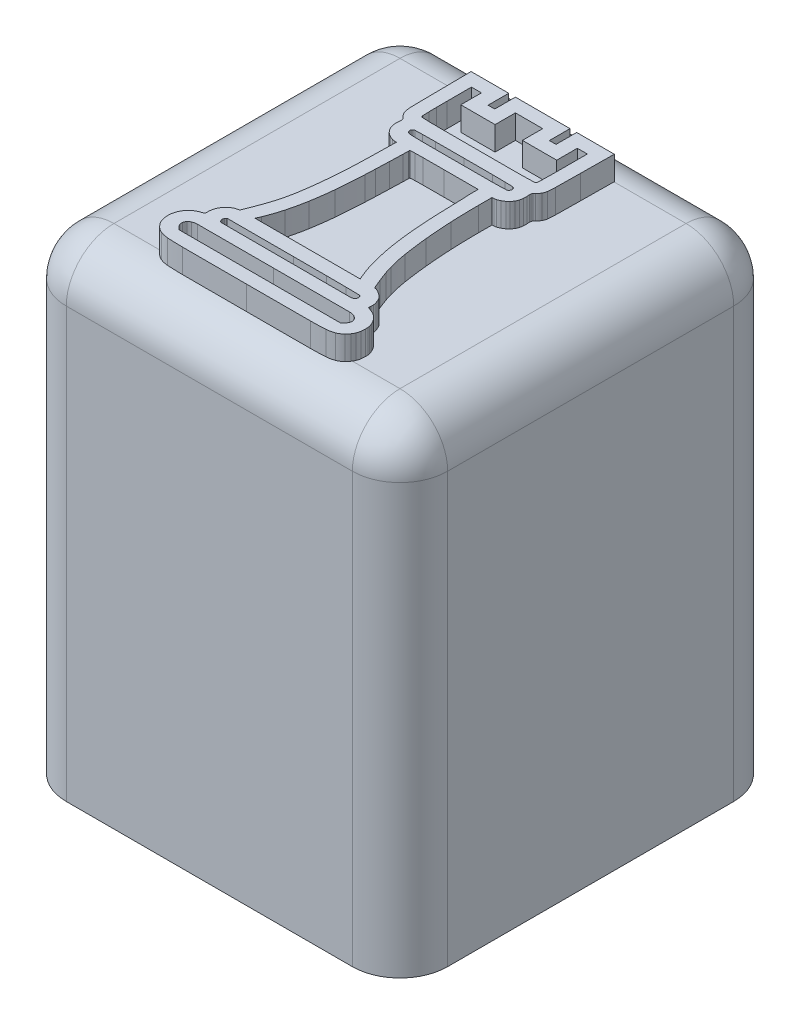
SolidWorks part; units mm, degrees
ref_plane "Front Plane" through (0, 0, 0) normal (0, 0, 1) x (1, 0, 0)
ref_plane "Top Plane" through (0, 0, 0) normal (0, 1, 0) x (1, 0, 0)
ref_plane "Right Plane" through (0, 0, 0) normal (1, 0, 0) x (0, 0, -1)
sketch "Sketch1" plane through (0, 0, 0) normal (0, 1, 0) x (1, 0, 0)
  line L1 (-20, -20) -> (20, -20)
  line L2 (-20, -20) -> (-20, 20)
  line L3 (-20, 20) -> (20, 20)
  line L4 (20, -20) -> (20, 20)
  line L5 (-20, -20) -> (20, 20) construction
  line L6 (-20, 20) -> (20, -20) construction
  point P0 (0, 0)
  dimension "D2" = 40
extrude "Boss-Extrude1" add sketch "Sketch1" along normal blind 50
sketch "Sketch3" plane through (0, 0, 20) normal (0, 0, 1) x (1, 0, 0)
  line L0 (1.0561, 36.7075) -> (0.9772, 36.8998)
  line L1 (0.9774, 38.7546) -> (1.0555, 38.9568)
  line L2 (1.2636, 39.4616) -> (1.5583, 40.149)
  line L3 (1.5583, 40.149) -> (1.0386, 40.149)
  line L4 (-0.0811, 29.649) -> (0.9618, 29.6463)
  line L5 (1.8583, 29.638) -> (2.6414, 29.6267)
  line L6 (2.7713, 21.6615) -> (2.7689, 25.299)
  line L7 (2.7689, 25.299) -> (0.1439, 25.299)
  line L8 (0.1439, 25.299) -> (-2.4811, 25.299)
  line L9 (-2.4811, 25.299) -> (-2.4811, 20.3238)
  arc A0 (-0.2519, 40.3197) -> (-0.2311, 40.524) centre (-1.2451, 40.524) ccw
  arc A1 (-0.3211, 40.2133) -> (-0.2519, 40.3197) centre (-0.4221, 40.3547) ccw
  arc A2 (-0.4612, 40.1616) -> (-0.3211, 40.2133) centre (-0.4854, 40.4434) ccw
  arc A3 (-0.7561, 40.149) -> (-0.4612, 40.1616) centre (-0.7561, 43.5923) ccw
  arc A4 (-0.7561, 40.149) -> (-0.9573, 40.1432) centre (-0.7561, 36.6752) ccw
  arc A5 (-0.9573, 40.1432) -> (-1.1268, 40.1252) centre (-0.8534, 38.3523) ccw
  arc A6 (-1.1268, 40.1252) -> (-1.2559, 40.0999) centre (-0.8815, 38.5344) ccw
  arc A7 (-1.2559, 40.0999) -> (-1.2811, 40.068) centre (-1.2483, 40.068) ccw
  arc A8 (-1.2811, 40.068) -> (-1.2699, 40.014) centre (-1.1443, 40.068) ccw
  arc A9 (-1.2699, 40.014) -> (-1.1899, 39.8321) centre (9.5694, 44.6764) ccw
  arc A10 (-1.1899, 39.8321) -> (-1.0895, 39.6175) centre (6.3479, 43.2259) ccw
  arc A11 (-1.0895, 39.6175) -> (-0.9706, 39.3785) centre (10.9024, 45.4356) ccw
  arc A12 (-0.8568, 39.1401) -> (-0.9706, 39.3785) centre (-5.47, 37.083) ccw
  arc A13 (-0.7722, 38.9279) -> (-0.8568, 39.1401) centre (-3.4493, 37.9841) ccw
  arc A14 (-0.7168, 38.7539) -> (-0.7722, 38.9279) centre (-3.5682, 37.9422) ccw
  arc A15 (-0.786, 38.6847) -> (-0.7168, 38.7539) centre (-0.7706, 38.7386) ccw
  arc A16 (-0.9599, 38.7401) -> (-0.786, 38.6847) centre (0.0258, 41.5361) ccw
  arc A17 (-1.1722, 38.8247) -> (-0.9599, 38.7401) centre (-0.0162, 41.4172) ccw
  arc A18 (-1.4106, 38.9385) -> (-1.1722, 38.8247) centre (0.8849, 43.438) ccw
  arc A19 (-1.4106, 38.9385) -> (-1.6496, 39.0575) centre (-7.4677, 27.0655) ccw
  arc A20 (-1.6496, 39.0575) -> (-1.8641, 39.1578) centre (-5.258, 31.6201) ccw
  arc A21 (-1.8641, 39.1578) -> (-2.046, 39.2379) centre (-6.7085, 28.3986) ccw
  arc A22 (-2.046, 39.2379) -> (-2.1001, 39.249) centre (-2.1001, 39.1122) ccw
  arc A23 (-2.1001, 39.249) -> (-2.1328, 39.2187) centre (-2.1001, 39.2162) ccw
  arc A24 (-2.1328, 39.2187) -> (-2.1573, 38.8524) centre (24.2016, 37.2714) ccw
  arc A25 (-2.1573, 38.8524) -> (-2.1752, 38.4166) centre (9.4788, 38.1545) ccw
  arc A26 (-2.1752, 38.4166) -> (-2.1811, 37.899) centre (20.8356, 37.899) ccw
  arc A27 (-2.1811, 37.899) -> (-2.1711, 37.3389) centre (13.6346, 37.899) ccw
  arc A28 (-2.1711, 37.3389) -> (-2.1393, 36.9135) centre (3.2431, 37.5307) ccw
  arc A29 (-2.1393, 36.9135) -> (-2.093, 36.6045) centre (2.3609, 37.4296) ccw
  arc A30 (-2.093, 36.6045) -> (-2.0262, 36.549) centre (-2.0262, 36.6169) ccw
  arc A31 (-2.0262, 36.549) -> (-1.9361, 36.5614) centre (-2.0262, 36.8823) ccw
  arc A32 (-1.9361, 36.5614) -> (-1.7587, 36.6151) centre (-3.1901, 41.0258) ccw
  arc A33 (-1.7587, 36.6151) -> (-1.5505, 36.6878) centre (-3.2862, 41.3219) ccw
  arc A34 (-1.5505, 36.6878) -> (-1.3329, 36.774) centre (-3.7454, 42.5478) ccw
  arc A35 (-0.8447, 36.9735) -> (-1.3329, 36.774) centre (11.7781, 5.3949) ccw
  arc A36 (-0.755, 36.9647) -> (-0.8447, 36.9735) centre (-0.8084, 36.8826) ccw
  arc A37 (-0.7353, 36.8934) -> (-0.755, 36.9647) centre (-0.7855, 36.9179) ccw
  arc A38 (-0.929, 36.5115) -> (-0.7353, 36.8934) centre (-14.8439, 43.8091) ccw
  arc A39 (-0.929, 36.5115) -> (-1.0335, 36.2868) centre (1.3559, 35.3132) ccw
  arc A40 (-1.0335, 36.2868) -> (-1.1357, 36.013) centre (3.5645, 34.4132) ccw
  arc A41 (-1.1357, 36.013) -> (-1.2212, 35.7353) centre (3.5282, 34.4256) ccw
  arc A42 (-1.2212, 35.7353) -> (-1.2736, 35.499) centre (1.0844, 35.0995) ccw
  arc A43 (-1.3377, 35.2022) -> (-1.2736, 35.499) centre (-4.6144, 36.065) ccw
  arc A44 (-1.4162, 35.0694) -> (-1.3377, 35.2022) centre (-1.6114, 35.2743) ccw
  arc A45 (-1.5421, 35.0151) -> (-1.4162, 35.0694) centre (-1.5526, 35.2126) ccw
  arc A46 (-1.7738, 35.0225) -> (-1.5421, 35.0151) centre (-1.6146, 36.3724) ccw
  arc A47 (-1.7738, 35.0225) -> (-2.2312, 35.0127) centre (-1.9675, 33.3797) ccw
  arc A48 (-2.2312, 35.0127) -> (-2.7326, 34.8813) centre (-1.8006, 32.3462) ccw
  arc A49 (-2.7326, 34.8813) -> (-3.1768, 34.6663) centre (-1.8677, 32.5287) ccw
  arc A50 (-3.1768, 34.6663) -> (-3.4556, 34.4041) centre (-2.6862, 33.8653) ccw
  arc A51 (-3.4556, 34.4041) -> (-3.6296, 34.0009) centre (-2.5658, 33.7809) ccw
  arc A52 (-3.6296, 34.0009) -> (-3.6625, 33.5003) centre (-1.8487, 33.6326) ccw
  arc A53 (-3.6625, 33.5003) -> (-3.5519, 32.8907) centre (-0.7619, 33.7118) ccw
  arc A54 (-3.5519, 32.8907) -> (-3.2917, 32.157) centre (3.2943, 34.9056) ccw
  arc A55 (-3.2917, 32.157) -> (-2.8071, 31.1489) centre (6.5018, 36.2442) ccw
  arc A56 (-2.8071, 31.1489) -> (-2.3873, 30.746) centre (-1.9574, 31.6139) ccw
  arc A57 (-2.3873, 30.746) -> (-1.7382, 30.581) centre (-1.6778, 32.1786) ccw
  arc A58 (-1.7382, 30.581) -> (-0.0451, 30.549) centre (-0.0451, 75.3343) ccw
  arc A59 (-0.0451, 30.549) -> (0.88, 30.5601) centre (-0.0451, 69.1084) ccw
  arc A60 (0.88, 30.5601) -> (1.655, 30.5944) centre (0.4199, 49.7291) ccw
  arc A61 (1.655, 30.5944) -> (2.2683, 30.6442) centre (0.4588, 49.1277) ccw
  arc A62 (2.2683, 30.6442) -> (2.495, 30.7129) centre (2.2094, 31.2467) ccw
  arc A63 (2.495, 30.7129) -> (2.8323, 31.0462) centre (2.1012, 31.4489) ccw
  arc A64 (2.8323, 31.0462) -> (3.306, 31.9836) centre (-10.1517, 38.1963) ccw
  arc A65 (3.306, 31.9836) -> (3.7093, 32.9611) centre (-8.3537, 37.3663) ccw
  arc A66 (3.7093, 32.9611) -> (3.8189, 33.5808) centre (2.0124, 33.5808) ccw
  arc A67 (3.8189, 33.5808) -> (3.8024, 33.7964) centre (2.4037, 33.5808) ccw
  arc A68 (3.8024, 33.7964) -> (3.7527, 34.0295) centre (1.7413, 33.4787) ccw
  arc A69 (3.7527, 34.0295) -> (3.68, 34.2449) centre (1.8744, 33.5151) ccw
  arc A70 (3.68, 34.2449) -> (3.5935, 34.4041) centre (2.9379, 33.945) ccw
  arc A71 (3.5935, 34.4041) -> (3.3105, 34.6687) centre (2.8257, 33.8664) ccw
  arc A72 (3.3105, 34.6687) -> (2.8545, 34.887) centre (1.9581, 32.4304) ccw
  arc A73 (2.8545, 34.887) -> (2.3545, 35.0167) centre (1.9319, 32.3586) ccw
  arc A74 (2.3545, 35.0167) -> (1.9327, 35.0101) centre (2.1624, 33.8084) ccw
  arc A75 (1.7458, 34.9882) -> (1.9327, 35.0101) centre (1.6872, 36.2945) ccw
  arc A76 (1.6409, 35.0177) -> (1.7458, 34.9882) centre (1.738, 35.1619) ccw
  arc A77 (1.5843, 35.1) -> (1.6409, 35.0177) centre (1.7168, 35.1304) ccw
  arc A78 (1.5656, 35.2573) -> (1.5843, 35.1) centre (2.3026, 35.265) ccw
  arc A79 (1.5656, 35.2573) -> (1.5452, 35.4219) centre (0.8313, 35.2497) ccw
  arc A80 (1.5452, 35.4219) -> (1.4762, 35.673) centre (-2.4739, 34.4521) ccw
  arc A81 (1.4762, 35.673) -> (1.3795, 35.9543) centre (-3.0532, 34.2731) ccw
  arc A82 (1.3795, 35.9543) -> (1.2656, 36.2279) centre (-2.9873, 34.298) ccw
  arc A83 (1.1519, 36.4828) -> (1.2656, 36.2279) centre (20.809, 45.0959) ccw
  arc A84 (1.0561, 36.7075) -> (1.1519, 36.4828) centre (12.6957, 41.5409) ccw
  arc A85 (0.9689, 36.9424) -> (0.9772, 36.8998) centre (1.0825, 36.9424) ccw
  arc A86 (0.9892, 36.958) -> (0.9689, 36.9424) centre (0.9851, 36.9424) ccw
  arc A87 (1.1285, 36.9185) -> (0.9892, 36.958) centre (0.1159, 33.6118) ccw
  arc A88 (1.3039, 36.8587) -> (1.1285, 36.9185) centre (0.2663, 34.1028) ccw
  arc A89 (1.5123, 36.776) -> (1.3039, 36.8587) centre (-0.9088, 30.9815) ccw
  arc A90 (1.5123, 36.776) -> (1.7299, 36.6891) centre (4.3642, 43.6017) ccw
  arc A91 (1.7299, 36.6891) -> (1.9347, 36.6157) centre (3.6828, 41.8136) ccw
  arc A92 (1.9347, 36.6157) -> (2.1078, 36.5606) centre (3.6736, 41.7863) ccw
  arc A93 (2.1078, 36.5606) -> (2.1873, 36.549) centre (2.1873, 36.8259) ccw
  arc A94 (2.1873, 36.549) -> (2.2398, 36.595) centre (2.1873, 36.602) ccw
  arc A95 (2.2398, 36.595) -> (2.2803, 36.9456) centre (-7.6131, 37.9106) ccw
  arc A96 (2.2803, 36.9456) -> (2.3095, 37.3814) centre (-4.8906, 37.645) ccw
  arc A97 (2.3095, 37.3814) -> (2.3189, 37.899) centre (-11.827, 37.899) ccw
  arc A98 (2.3189, 37.899) -> (2.3131, 38.4166) centre (-20.6977, 37.899) ccw
  arc A99 (2.3131, 38.4166) -> (2.2951, 38.8524) centre (-9.3409, 38.1545) ccw
  arc A100 (2.2951, 38.8524) -> (2.2706, 39.2187) centre (-24.0637, 37.2714) ccw
  arc A101 (2.2706, 39.2187) -> (2.238, 39.249) centre (2.238, 39.2162) ccw
  arc A102 (2.238, 39.249) -> (2.1841, 39.238) centre (2.238, 39.1121) ccw
  arc A103 (2.1841, 39.238) -> (2.0063, 39.16) centre (6.555, 29.0283) ccw
  arc A104 (2.0063, 39.16) -> (1.7964, 39.062) centre (5.2502, 31.9346) ccw
  arc A105 (1.7964, 39.062) -> (1.563, 38.9459) centre (7.3387, 27.6246) ccw
  arc A106 (1.3351, 38.8344) -> (1.563, 38.9459) centre (-1.9375, 45.8074) ccw
  arc A107 (1.1434, 38.7512) -> (1.3351, 38.8344) centre (-0.1812, 42.0652) ccw
  arc A108 (0.9904, 38.6934) -> (1.1434, 38.7512) centre (-0.4615, 42.7665) ccw
  arc A109 (0.9689, 38.7085) -> (0.9904, 38.6934) centre (0.985, 38.7085) ccw
  arc A110 (0.9774, 38.7546) -> (0.9689, 38.7085) centre (1.0984, 38.7085) ccw
  arc A111 (1.1507, 39.1934) -> (1.0555, 38.9568) centre (13.4954, 34.089) ccw
  arc A112 (1.2636, 39.4616) -> (1.1507, 39.1934) centre (22.0216, 30.5636) ccw
  arc A113 (0.7475, 40.1618) -> (1.0386, 40.149) centre (1.0386, 43.4741) ccw
  arc A114 (0.6084, 40.2136) -> (0.7475, 40.1618) centre (0.772, 40.4403) ccw
  arc A115 (0.5396, 40.32) -> (0.6084, 40.2136) centre (0.7105, 40.355) ccw
  arc A116 (0.5189, 40.524) -> (0.5396, 40.32) centre (1.5361, 40.524) ccw
  arc A117 (0.5189, 40.524) -> (0.5016, 40.7143) centre (-0.5324, 40.524) ccw
  arc A118 (0.5016, 40.7143) -> (0.3342, 40.8816) centre (0.2965, 40.6765) ccw
  arc A119 (0.3342, 40.8816) -> (-0.0463, 40.8816) centre (0.1439, 39.8476) ccw
  arc A120 (-0.0463, 40.8816) -> (-0.2137, 40.7143) centre (-0.0086, 40.6765) ccw
  arc A121 (-0.2137, 40.7143) -> (-0.2311, 40.524) centre (0.8203, 40.524) ccw
  arc A122 (-2.7811, 29.874) -> (-2.6834, 29.7509) centre (-2.6547, 29.874) ccw
  arc A123 (-2.6834, 29.7509) -> (-2.2936, 29.6896) centre (-2.0684, 32.3915) ccw
  arc A124 (-2.2936, 29.6896) -> (-1.5802, 29.6564) centre (-1.4837, 39.4081) ccw
  arc A125 (-1.5802, 29.6564) -> (-0.0811, 29.649) centre (-0.081, 181.1989) ccw
  arc A126 (1.8583, 29.638) -> (0.9618, 29.6463) centre (0.3904, -80.3732) ccw
  arc A127 (2.7294, 29.6115) -> (2.6414, 29.6267) centre (2.637, 29.3393) ccw
  arc A128 (2.7294, 29.6115) -> (2.7754, 29.6173) centre (2.7464, 29.6617) ccw
  arc A129 (2.7754, 29.6173) -> (2.8222, 29.6621) centre (2.6798, 29.7641) ccw
  arc A130 (2.8222, 29.6621) -> (2.863, 29.7387) centre (2.5549, 29.8534) ccw
  arc A131 (2.863, 29.7387) -> (2.8904, 29.8365) centre (2.2897, 29.9522) ccw
  arc A132 (2.8904, 29.8365) -> (2.8098, 29.9833) centre (2.7616, 29.8613) ccw
  arc A133 (2.8098, 29.9833) -> (2.4942, 30.0587) centre (2.3872, 28.9131) ccw
  arc A134 (2.4942, 30.0587) -> (1.8188, 30.0927) centre (1.7613, 22.2127) ccw
  arc A135 (1.8188, 30.0927) -> (0.0799, 30.099) centre (0.0798, -208.4943) ccw
  arc A136 (0.0799, 30.099) -> (-1.5127, 30.0916) centre (0.0801, -142.3417) ccw
  arc A137 (-1.5127, 30.0916) -> (-2.2667, 30.0585) centre (-1.412, 19.1902) ccw
  arc A138 (-2.2667, 30.0585) -> (-2.681, 29.9979) centre (-2.0209, 26.9332) ccw
  arc A139 (-2.681, 29.9979) -> (-2.7811, 29.874) centre (-2.6543, 29.874) ccw
  arc A140 (-3.2011, 28.869) -> (-3.3415, 28.6498) centre (-2.7707, 28.4386) ccw
  arc A141 (-3.3415, 28.6498) -> (-3.37, 28.4009) centre (-2.8483, 28.4673) ccw
  arc A142 (-3.37, 28.4009) -> (-3.2802, 28.171) centre (-2.8665, 28.465) ccw
  arc A143 (-3.2802, 28.171) -> (-3.0909, 28.0043) centre (-2.8307, 28.4904) ccw
  arc A144 (-3.0909, 28.0043) -> (-2.8643, 27.9389) centre (-2.8249, 28.5013) ccw
  arc A145 (-2.8643, 27.9389) -> (-2.0811, 27.8923) centre (-0.2241, 65.6821) ccw
  arc A146 (-2.0811, 27.8923) -> (-1.1052, 27.8596) centre (-0.5401, 59.2505) ccw
  arc A147 (-1.1052, 27.8596) -> (0.0689, 27.849) centre (0.069, 93.0962) ccw
  arc A148 (0.0689, 27.849) -> (1.2431, 27.8596) centre (0.0689, 93.0962) ccw
  arc A149 (1.2431, 27.8596) -> (2.219, 27.8923) centre (0.678, 59.2505) ccw
  arc A150 (2.219, 27.8923) -> (3.0021, 27.9389) centre (0.362, 65.6821) ccw
  arc A151 (3.0021, 27.9389) -> (3.2288, 28.0043) centre (2.9628, 28.5013) ccw
  arc A152 (3.2288, 28.0043) -> (3.4181, 28.171) centre (2.9686, 28.4904) ccw
  arc A153 (3.4181, 28.171) -> (3.5078, 28.4009) centre (3.0044, 28.465) ccw
  arc A154 (3.5078, 28.4009) -> (3.4794, 28.6498) centre (2.9862, 28.4673) ccw
  arc A155 (3.4794, 28.6498) -> (3.3389, 28.869) centre (2.9086, 28.4386) ccw
  arc A156 (3.3389, 28.869) -> (2.9205, 29.0449) centre (2.9141, 28.4442) ccw
  arc A157 (2.9205, 29.0449) -> (0.0689, 29.06) centre (0.0692, -241.1828) ccw
  arc A158 (0.0689, 29.06) -> (-2.7826, 29.0449) centre (0.0687, -241.1828) ccw
  arc A159 (-2.7826, 29.0449) -> (-3.2011, 28.869) centre (-2.7763, 28.4442) ccw
  arc A160 (-3.1328, 27.1247) -> (-3.3122, 26.8437) centre (-2.3914, 26.4538) ccw
  arc A161 (-3.3122, 26.8437) -> (-3.3698, 26.5418) centre (-2.6392, 26.5587) ccw
  arc A162 (-3.3698, 26.5418) -> (-3.2979, 26.25) centre (-2.6767, 26.5578) ccw
  arc A163 (-3.2979, 26.25) -> (-3.1068, 25.9972) centre (-2.5367, 26.6272) ccw
  arc A164 (-3.1068, 25.9972) -> (-2.8436, 25.8628) centre (-2.7259, 26.418) ccw
  arc A165 (-2.8436, 25.8628) -> (-2.3601, 25.7932) centre (-2.0725, 29.5022) ccw
  arc A166 (-2.3601, 25.7932) -> (-1.5419, 25.7573) centre (-1.4176, 37.9496) ccw
  arc A167 (-1.5419, 25.7573) -> (0.095, 25.749) centre (0.0951, 186.3559) ccw
  arc A168 (0.095, 25.749) -> (1.8232, 25.7567) centre (0.0951, 220.1037) ccw
  arc A169 (1.8232, 25.7567) -> (2.5908, 25.7932) centre (1.7347, 35.7037) ccw
  arc A170 (2.5908, 25.7932) -> (3.0223, 25.8704) centre (2.3832, 28.1963) ccw
  arc A171 (3.0223, 25.8704) -> (3.2707, 26.0233) centre (2.8842, 26.3731) ccw
  arc A172 (3.2707, 26.0233) -> (3.4501, 26.3043) centre (2.5293, 26.6942) ccw
  arc A173 (3.4501, 26.3043) -> (3.5077, 26.6062) centre (2.7771, 26.5893) ccw
  arc A174 (3.5077, 26.6062) -> (3.4358, 26.898) centre (2.8146, 26.5902) ccw
  arc A175 (3.4358, 26.898) -> (3.2446, 27.1507) centre (2.6745, 26.5208) ccw
  arc A176 (3.2446, 27.1507) -> (2.9814, 27.2852) centre (2.8638, 26.7299) ccw
  arc A177 (2.9814, 27.2852) -> (2.498, 27.3548) centre (2.2104, 23.6458) ccw
  arc A178 (2.498, 27.3548) -> (1.6797, 27.3907) centre (1.5555, 15.1984) ccw
  arc A179 (1.6797, 27.3907) -> (0.0429, 27.399) centre (0.0428, -133.2079) ccw
  arc A180 (0.0429, 27.399) -> (-1.6853, 27.3913) centre (0.0428, -166.9557) ccw
  arc A181 (-1.6853, 27.3913) -> (-2.4529, 27.3548) centre (-1.5969, 17.4443) ccw
  arc A182 (-2.4529, 27.3548) -> (-2.8844, 27.2775) centre (-2.2453, 24.9517) ccw
  arc A183 (-2.8844, 27.2775) -> (-3.1328, 27.1247) centre (-2.7463, 26.7749) ccw
  arc A184 (-2.5058, 16.8148) -> (-2.4811, 20.3238) centre (-251.3554, 20.324) ccw
  arc A185 (-2.6074, 14.9611) -> (-2.5058, 16.8148) centre (-25.3573, 17.1371) ccw
  arc A186 (-2.8188, 13.7542) -> (-2.6074, 14.9611) centre (-10.4289, 15.7092) ccw
  arc A187 (-3.2028, 12.7776) -> (-2.8188, 13.7542) centre (-6.9535, 14.8164) ccw
  arc A188 (-3.6046, 12.1943) -> (-3.2028, 12.7776) centre (-6.1658, 14.3883) ccw
  arc A189 (-4.1668, 11.6285) -> (-3.6046, 12.1943) centre (-7.7031, 15.7051) ccw
  arc A190 (-4.7738, 11.1774) -> (-4.1668, 11.6285) centre (-7.4556, 15.4198) ccw
  arc A191 (-5.3054, 10.9537) -> (-4.7738, 11.1774) centre (-5.7095, 12.6576) ccw
  arc A192 (-5.3054, 10.9537) -> (-5.8439, 10.7189) centre (-4.9231, 9.342) ccw
  arc A193 (-5.8439, 10.7189) -> (-6.1667, 10.3364) centre (-5.3411, 9.9671) ccw
  arc A194 (-6.1667, 10.3364) -> (-6.2016, 9.8977) centre (-5.5668, 10.068) ccw
  arc A195 (-6.2016, 9.8977) -> (-5.9568, 9.4972) centre (-5.3996, 10.1129) ccw
  arc A196 (-5.9568, 9.4972) -> (-5.6326, 9.3524) centre (-5.5728, 9.9215) ccw
  arc A197 (-5.6326, 9.3524) -> (-4.776, 9.2899) centre (-4.2238, 22.7511) ccw
  arc A198 (-4.776, 9.2899) -> (-3.2804, 9.2561) centre (-3.1097, 49.9101) ccw
  arc A199 (-3.2804, 9.2561) -> (0.095, 9.249) centre (0.0949, 812.9143) ccw
  arc A200 (0.095, 9.249) -> (3.6487, 9.2555) centre (0.0957, 981.2603) ccw
  arc A201 (3.6487, 9.2555) -> (5.0482, 9.2899) centre (3.5264, 42.7187) ccw
  arc A202 (5.0482, 9.2899) -> (5.8101, 9.3593) centre (4.6649, 17.7092) ccw
  arc A203 (5.8101, 9.3593) -> (6.1207, 9.5233) centre (5.7404, 9.8674) ccw
  arc A204 (6.1207, 9.5233) -> (6.3473, 9.9262) centre (5.3468, 10.2237) ccw
  arc A205 (6.3473, 9.9262) -> (6.3187, 10.3119) centre (5.8251, 10.0815) ccw
  arc A206 (6.3187, 10.3119) -> (6.0117, 10.6859) centre (5.435, 9.8993) ccw
  arc A207 (6.0117, 10.6859) -> (5.4054, 11.0555) centre (3.5441, 7.3203) ccw
  arc A208 (4.9054, 11.425) -> (5.4054, 11.0555) centre (6.2054, 12.6608) ccw
  arc A209 (4.2938, 12.1416) -> (4.9054, 11.425) centre (11.2766, 17.4818) ccw
  arc A210 (3.7311, 12.9678) -> (4.2938, 12.1416) centre (11.5249, 17.6717) ccw
  arc A211 (3.3645, 13.7241) -> (3.7311, 12.9678) centre (7.6599, 15.339) ccw
  arc A212 (3.0948, 14.7817) -> (3.3645, 13.7241) centre (8.0224, 15.4753) ccw
  arc A213 (2.9159, 16.444) -> (3.0948, 14.7817) centre (28.4803, 18.3546) ccw
  arc A214 (2.8066, 18.6815) -> (2.9159, 16.444) centre (46.2293, 19.6812) ccw
  arc A215 (2.7713, 21.6615) -> (2.8066, 18.6815) centre (136.0335, 21.7485) ccw
  arc A216 (-6.8953, 8.4133) -> (-7.0747, 8.1313) centre (-6.351, 7.8689) ccw
  arc A217 (-7.0747, 8.1313) -> (-7.1192, 7.7981) centre (-6.3348, 7.863) ccw
  arc A218 (-7.1192, 7.7981) -> (-7.0206, 7.478) centre (-6.3408, 7.8625) ccw
  arc A219 (-7.0206, 7.478) -> (-6.7977, 7.2325) centre (-6.3666, 7.8479) ccw
  arc A220 (-6.7977, 7.2325) -> (-6.4238, 7.0983) centre (-6.3648, 7.8505) ccw
  arc A221 (-6.4238, 7.0983) -> (-5.3822, 7.0397) centre (-4.5818, 30.5776) ccw
  arc A222 (-5.3822, 7.0397) -> (-3.628, 7.0064) centre (-3.3932, 65.5325) ccw
  arc A223 (-3.628, 7.0064) -> (0.0689, 6.999) centre (0.0688, 928.4798) ccw
  arc A224 (0.0689, 6.999) -> (4.7905, 7.0137) centre (0.0687, 764.6331) ccw
  arc A225 (4.7905, 7.0137) -> (6.3305, 7.1062) centre (4.701, 21.3654) ccw
  arc A226 (6.3305, 7.1062) -> (7.0124, 7.3504) centre (6.1502, 8.6838) ccw
  arc A227 (7.0124, 7.3504) -> (7.2689, 7.8218) centre (6.7076, 7.8218) ccw
  arc A228 (7.2689, 7.8218) -> (7.0294, 8.3034) centre (6.6651, 7.8218) ccw
  arc A229 (7.0294, 8.3034) -> (6.4123, 8.5506) centre (6.2683, 7.2972) ccw
  arc A230 (6.4123, 8.5506) -> (4.9732, 8.6366) centre (4.9066, -4.5546) ccw
  arc A231 (4.9732, 8.6366) -> (0.0689, 8.649) centre (0.0685, -962.8832) ccw
  arc A232 (0.0689, 8.649) -> (-3.7934, 8.6419) centre (0.0689, -1042.0477) ccw
  arc A233 (-3.7934, 8.6419) -> (-5.5543, 8.6089) centre (-3.5787, -49.7641) ccw
  arc A234 (-5.5543, 8.6089) -> (-6.5926, 8.5522) centre (-4.7026, -16.556) ccw
  arc A235 (-6.5926, 8.5522) -> (-6.8953, 8.4133) centre (-6.5566, 8.0745) ccw
extrude "Cut-Extrude1" [suppressed] cut sketch "Sketch3" against normal blind 5
pattern_circular "CirPattern1" [suppressed] count 4 over 360 of bodies 102
pattern_circular "CirPattern2" [suppressed] count 2 over 90 reverse direction yes of bodies 102
fillet "Fillet2" radius 5 8 edges at (0, 50, 20) (-20, 50, 0) (0, 50, -20) (20, 50, 0) (20, 25, -20) (-20, 25, -20) (-20, 25, 20) (20, 25, 20)
sketch "Sketch4" plane through (0, 50, 0) normal (0, 1, 0) x (1, 0, 0)
  line L0 (0.2801, 12.8673) -> (0.2013, 13.0596)
  line L1 (0.2014, 14.9145) -> (0.2795, 15.1166)
  line L2 (0.4876, 15.6214) -> (0.7823, 16.3089)
  line L3 (0.7823, 16.3089) -> (0.2626, 16.3089)
  line L4 (-0.8571, 5.8089) -> (0.1859, 5.8061)
  line L5 (1.0823, 5.7978) -> (1.8654, 5.7866)
  line L6 (1.9953, -2.1786) -> (1.9929, 1.4589)
  line L7 (1.9929, 1.4589) -> (-0.6321, 1.4589)
  line L8 (-0.6321, 1.4589) -> (-3.2571, 1.4589)
  line L9 (-3.2571, 1.4589) -> (-3.2571, -3.5164)
  arc A0 (-1.0279, 16.4795) -> (-1.0071, 16.6839) centre (-2.0211, 16.6839) ccw
  arc A1 (-1.0971, 16.3731) -> (-1.0279, 16.4795) centre (-1.198, 16.5145) ccw
  arc A2 (-1.2372, 16.3215) -> (-1.0971, 16.3731) centre (-1.2614, 16.6033) ccw
  arc A3 (-1.5321, 16.3089) -> (-1.2372, 16.3215) centre (-1.5321, 19.7522) ccw
  arc A4 (-1.5321, 16.3089) -> (-1.7333, 16.303) centre (-1.532, 12.8351) ccw
  arc A5 (-1.7333, 16.303) -> (-1.9028, 16.2851) centre (-1.6294, 14.5122) ccw
  arc A6 (-1.9028, 16.2851) -> (-2.0319, 16.2597) centre (-1.6575, 14.6943) ccw
  arc A7 (-2.0319, 16.2597) -> (-2.0571, 16.2279) centre (-2.0243, 16.2279) ccw
  arc A8 (-2.0571, 16.2279) -> (-2.0459, 16.1738) centre (-1.9203, 16.2279) ccw
  arc A9 (-2.0459, 16.1738) -> (-1.9659, 15.9919) centre (8.7934, 20.8363) ccw
  arc A10 (-1.9659, 15.9919) -> (-1.8655, 15.7774) centre (5.5719, 19.3858) ccw
  arc A11 (-1.8655, 15.7774) -> (-1.7466, 15.5383) centre (10.1264, 21.5955) ccw
  arc A12 (-1.6327, 15.3) -> (-1.7466, 15.5383) centre (-6.246, 13.2429) ccw
  arc A13 (-1.5482, 15.0877) -> (-1.6327, 15.3) centre (-4.2253, 14.144) ccw
  arc A14 (-1.4928, 14.9138) -> (-1.5482, 15.0877) centre (-4.3442, 14.102) ccw
  arc A15 (-1.562, 14.8446) -> (-1.4928, 14.9138) centre (-1.5466, 14.8984) ccw
  arc A16 (-1.7359, 14.9) -> (-1.562, 14.8446) centre (-0.7502, 17.696) ccw
  arc A17 (-1.9482, 14.9845) -> (-1.7359, 14.9) centre (-0.7922, 17.5771) ccw
  arc A18 (-2.1865, 15.0984) -> (-1.9482, 14.9845) centre (0.1089, 19.5978) ccw
  arc A19 (-2.1865, 15.0984) -> (-2.4256, 15.2173) centre (-8.2437, 3.2254) ccw
  arc A20 (-2.4256, 15.2173) -> (-2.6401, 15.3177) centre (-6.034, 7.7799) ccw
  arc A21 (-2.6401, 15.3177) -> (-2.822, 15.3977) centre (-7.4845, 4.5584) ccw
  arc A22 (-2.822, 15.3977) -> (-2.8761, 15.4089) centre (-2.8761, 15.2721) ccw
  arc A23 (-2.8761, 15.4089) -> (-2.9087, 15.3785) centre (-2.8761, 15.3761) ccw
  arc A24 (-2.9087, 15.3785) -> (-2.9333, 15.0123) centre (23.4256, 13.4312) ccw
  arc A25 (-2.9333, 15.0123) -> (-2.9512, 14.5765) centre (8.7028, 14.3143) ccw
  arc A26 (-2.9512, 14.5765) -> (-2.9571, 14.0589) centre (20.0596, 14.0589) ccw
  arc A27 (-2.9571, 14.0589) -> (-2.9471, 13.4987) centre (12.8586, 14.0588) ccw
  arc A28 (-2.9471, 13.4987) -> (-2.9152, 13.0733) centre (2.4671, 13.6906) ccw
  arc A29 (-2.9152, 13.0733) -> (-2.869, 12.7644) centre (1.5849, 13.5894) ccw
  arc A30 (-2.869, 12.7644) -> (-2.8022, 12.7089) centre (-2.8022, 12.7767) ccw
  arc A31 (-2.8022, 12.7089) -> (-2.7121, 12.7213) centre (-2.8022, 13.0421) ccw
  arc A32 (-2.7121, 12.7213) -> (-2.5347, 12.7749) centre (-3.9661, 17.1857) ccw
  arc A33 (-2.5347, 12.7749) -> (-2.3264, 12.8477) centre (-4.0622, 17.4817) ccw
  arc A34 (-2.3264, 12.8477) -> (-2.1089, 12.9339) centre (-4.5214, 18.7077) ccw
  arc A35 (-1.6207, 13.1334) -> (-2.1089, 12.9339) centre (11.0021, -18.4453) ccw
  arc A36 (-1.531, 13.1246) -> (-1.6207, 13.1334) centre (-1.5844, 13.0425) ccw
  arc A37 (-1.5113, 13.0532) -> (-1.531, 13.1246) centre (-1.5614, 13.0778) ccw
  arc A38 (-1.705, 12.6714) -> (-1.5113, 13.0532) centre (-15.6199, 19.969) ccw
  arc A39 (-1.705, 12.6714) -> (-1.8094, 12.4466) centre (0.5799, 11.473) ccw
  arc A40 (-1.8094, 12.4466) -> (-1.9117, 12.1728) centre (2.7885, 10.5731) ccw
  arc A41 (-1.9117, 12.1728) -> (-1.9972, 11.8952) centre (2.7522, 10.5854) ccw
  arc A42 (-1.9972, 11.8952) -> (-2.0496, 11.6589) centre (0.3084, 11.2594) ccw
  arc A43 (-2.1137, 11.3621) -> (-2.0496, 11.6589) centre (-5.3904, 12.2248) ccw
  arc A44 (-2.1922, 11.2292) -> (-2.1137, 11.3621) centre (-2.3874, 11.4342) ccw
  arc A45 (-2.3181, 11.1749) -> (-2.1922, 11.2292) centre (-2.3286, 11.3725) ccw
  arc A46 (-2.5498, 11.1823) -> (-2.3181, 11.1749) centre (-2.3906, 12.5323) ccw
  arc A47 (-2.5498, 11.1823) -> (-3.0072, 11.1726) centre (-2.7435, 9.5396) ccw
  arc A48 (-3.0072, 11.1726) -> (-3.5086, 11.0412) centre (-2.5766, 8.5061) ccw
  arc A49 (-3.5086, 11.0412) -> (-3.9528, 10.8261) centre (-2.6436, 8.6885) ccw
  arc A50 (-3.9528, 10.8261) -> (-4.2316, 10.564) centre (-3.4622, 10.0251) ccw
  arc A51 (-4.2316, 10.564) -> (-4.4056, 10.1608) centre (-3.3418, 9.9407) ccw
  arc A52 (-4.4056, 10.1608) -> (-4.4385, 9.6601) centre (-2.6247, 9.7924) ccw
  arc A53 (-4.4385, 9.6601) -> (-4.3279, 9.0506) centre (-1.5379, 9.8717) ccw
  arc A54 (-4.3279, 9.0506) -> (-4.0677, 8.3168) centre (2.5183, 11.0655) ccw
  arc A55 (-4.0677, 8.3168) -> (-3.5831, 7.3087) centre (5.7258, 12.4041) ccw
  arc A56 (-3.5831, 7.3087) -> (-3.1633, 6.9058) centre (-2.7334, 7.7738) ccw
  arc A57 (-3.1633, 6.9058) -> (-2.5142, 6.7409) centre (-2.4537, 8.3385) ccw
  arc A58 (-2.5142, 6.7409) -> (-0.821, 6.7089) centre (-0.8211, 51.4941) ccw
  arc A59 (-0.821, 6.7089) -> (0.104, 6.7199) centre (-0.8211, 45.2682) ccw
  arc A60 (0.104, 6.7199) -> (0.879, 6.7542) centre (-0.356, 25.8889) ccw
  arc A61 (0.879, 6.7542) -> (1.4923, 6.804) centre (-0.3172, 25.2875) ccw
  arc A62 (1.4923, 6.804) -> (1.719, 6.8728) centre (1.4334, 7.4065) ccw
  arc A63 (1.719, 6.8728) -> (2.0563, 7.2061) centre (1.3252, 7.6087) ccw
  arc A64 (2.0563, 7.2061) -> (2.53, 8.1434) centre (-10.9276, 14.3561) ccw
  arc A65 (2.53, 8.1434) -> (2.9333, 9.121) centre (-9.1297, 13.5261) ccw
  arc A66 (2.9333, 9.121) -> (3.0429, 9.7406) centre (1.2364, 9.7406) ccw
  arc A67 (3.0429, 9.7406) -> (3.0264, 9.9562) centre (1.6277, 9.7406) ccw
  arc A68 (3.0264, 9.9562) -> (2.9767, 10.1894) centre (0.9653, 9.6386) ccw
  arc A69 (2.9767, 10.1894) -> (2.904, 10.4047) centre (1.0984, 9.675) ccw
  arc A70 (2.904, 10.4047) -> (2.8175, 10.564) centre (2.1619, 10.1048) ccw
  arc A71 (2.8175, 10.564) -> (2.5345, 10.8285) centre (2.0498, 10.0263) ccw
  arc A72 (2.5345, 10.8285) -> (2.0785, 11.0469) centre (1.1821, 8.5902) ccw
  arc A73 (2.0785, 11.0469) -> (1.5785, 11.1766) centre (1.1559, 8.5185) ccw
  arc A74 (1.5785, 11.1766) -> (1.1567, 11.17) centre (1.3864, 9.9683) ccw
  arc A75 (0.9698, 11.148) -> (1.1567, 11.17) centre (0.9112, 12.4544) ccw
  arc A76 (0.8649, 11.1775) -> (0.9698, 11.148) centre (0.962, 11.3217) ccw
  arc A77 (0.8083, 11.2598) -> (0.8649, 11.1775) centre (0.9408, 11.2903) ccw
  arc A78 (0.7897, 11.4172) -> (0.8083, 11.2598) centre (1.5266, 11.4248) ccw
  arc A79 (0.7897, 11.4172) -> (0.7692, 11.5818) centre (0.0553, 11.4095) ccw
  arc A80 (0.7692, 11.5818) -> (0.7002, 11.8329) centre (-3.2498, 10.612) ccw
  arc A81 (0.7002, 11.8329) -> (0.6035, 12.1142) centre (-3.8291, 10.4329) ccw
  arc A82 (0.6035, 12.1142) -> (0.4897, 12.3877) centre (-3.7633, 10.4579) ccw
  arc A83 (0.376, 12.6427) -> (0.4897, 12.3877) centre (20.033, 21.2557) ccw
  arc A84 (0.2801, 12.8673) -> (0.376, 12.6427) centre (11.9197, 17.7008) ccw
  arc A85 (0.1929, 13.1022) -> (0.2013, 13.0596) centre (0.3065, 13.1022) ccw
  arc A86 (0.2132, 13.1179) -> (0.1929, 13.1022) centre (0.2091, 13.1022) ccw
  arc A87 (0.3525, 13.0784) -> (0.2132, 13.1179) centre (-0.6601, 9.7716) ccw
  arc A88 (0.5279, 13.0186) -> (0.3525, 13.0784) centre (-0.5097, 10.2627) ccw
  arc A89 (0.7363, 12.9359) -> (0.5279, 13.0186) centre (-1.6848, 7.1414) ccw
  arc A90 (0.7363, 12.9359) -> (0.954, 12.8489) centre (3.5882, 19.7616) ccw
  arc A91 (0.954, 12.8489) -> (1.1587, 12.7755) centre (2.9068, 17.9735) ccw
  arc A92 (1.1587, 12.7755) -> (1.3318, 12.7205) centre (2.8976, 17.9461) ccw
  arc A93 (1.3318, 12.7205) -> (1.4113, 12.7089) centre (1.4113, 12.9857) ccw
  arc A94 (1.4113, 12.7089) -> (1.4638, 12.7548) centre (1.4113, 12.7618) ccw
  arc A95 (1.4638, 12.7548) -> (1.5043, 13.1054) centre (-8.3891, 14.0704) ccw
  arc A96 (1.5043, 13.1054) -> (1.5335, 13.5412) centre (-5.6666, 13.8049) ccw
  arc A97 (1.5335, 13.5412) -> (1.5429, 14.0589) centre (-12.603, 14.0589) ccw
  arc A98 (1.5429, 14.0589) -> (1.5371, 14.5765) centre (-21.4737, 14.0589) ccw
  arc A99 (1.5371, 14.5765) -> (1.5192, 15.0123) centre (-10.1169, 14.3143) ccw
  arc A100 (1.5192, 15.0123) -> (1.4946, 15.3785) centre (-24.8397, 13.4312) ccw
  arc A101 (1.4946, 15.3785) -> (1.462, 15.4089) centre (1.462, 15.3761) ccw
  arc A102 (1.462, 15.4089) -> (1.4081, 15.3978) centre (1.462, 15.272) ccw
  arc A103 (1.4081, 15.3978) -> (1.2303, 15.3198) centre (5.779, 5.1882) ccw
  arc A104 (1.2303, 15.3198) -> (1.0204, 15.2219) centre (4.4742, 8.0944) ccw
  arc A105 (1.0204, 15.2219) -> (0.787, 15.1058) centre (6.5627, 3.7844) ccw
  arc A106 (0.5591, 14.9942) -> (0.787, 15.1058) centre (-2.7135, 21.9672) ccw
  arc A107 (0.3674, 14.911) -> (0.5591, 14.9942) centre (-0.9572, 18.2251) ccw
  arc A108 (0.2144, 14.8532) -> (0.3674, 14.911) centre (-1.2375, 18.9263) ccw
  arc A109 (0.1929, 14.8684) -> (0.2144, 14.8532) centre (0.209, 14.8684) ccw
  arc A110 (0.2014, 14.9145) -> (0.1929, 14.8684) centre (0.3224, 14.8684) ccw
  arc A111 (0.3747, 15.3532) -> (0.2795, 15.1166) centre (12.7194, 10.2489) ccw
  arc A112 (0.4876, 15.6214) -> (0.3747, 15.3532) centre (21.2456, 6.7235) ccw
  arc A113 (-0.0284, 16.3216) -> (0.2626, 16.3089) centre (0.2626, 19.634) ccw
  arc A114 (-0.1676, 16.3734) -> (-0.0284, 16.3216) centre (-0.004, 16.6001) ccw
  arc A115 (-0.2364, 16.4799) -> (-0.1676, 16.3734) centre (-0.0655, 16.5148) ccw
  arc A116 (-0.2571, 16.6839) -> (-0.2364, 16.4799) centre (0.7601, 16.6839) ccw
  arc A117 (-0.2571, 16.6839) -> (-0.2744, 16.8741) centre (-1.3084, 16.6839) ccw
  arc A118 (-0.2744, 16.8741) -> (-0.4418, 17.0415) centre (-0.4795, 16.8364) ccw
  arc A119 (-0.4418, 17.0415) -> (-0.8223, 17.0415) centre (-0.6321, 16.0075) ccw
  arc A120 (-0.8223, 17.0415) -> (-0.9897, 16.8741) centre (-0.7846, 16.8364) ccw
  arc A121 (-0.9897, 16.8741) -> (-1.0071, 16.6839) centre (0.0443, 16.6839) ccw
  arc A122 (-3.5571, 6.0339) -> (-3.4593, 5.9108) centre (-3.4307, 6.0339) ccw
  arc A123 (-3.4593, 5.9108) -> (-3.0696, 5.8495) centre (-2.8444, 8.5513) ccw
  arc A124 (-3.0696, 5.8495) -> (-2.3562, 5.8163) centre (-2.2597, 15.568) ccw
  arc A125 (-2.3562, 5.8163) -> (-0.8571, 5.8089) centre (-0.8569, 157.3588) ccw
  arc A126 (1.0823, 5.7978) -> (0.1859, 5.8061) centre (-0.3856, -104.2134) ccw
  arc A127 (1.9534, 5.7714) -> (1.8654, 5.7866) centre (1.861, 5.4992) ccw
  arc A128 (1.9534, 5.7714) -> (1.9994, 5.7771) centre (1.9704, 5.8216) ccw
  arc A129 (1.9994, 5.7771) -> (2.0462, 5.822) centre (1.9038, 5.9239) ccw
  arc A130 (2.0462, 5.822) -> (2.087, 5.8986) centre (1.7789, 6.0133) ccw
  arc A131 (2.087, 5.8986) -> (2.1144, 5.9964) centre (1.5137, 6.112) ccw
  arc A132 (2.1144, 5.9964) -> (2.0338, 6.1432) centre (1.9856, 6.0212) ccw
  arc A133 (2.0338, 6.1432) -> (1.7182, 6.2186) centre (1.6112, 5.0729) ccw
  arc A134 (1.7182, 6.2186) -> (1.0428, 6.2525) centre (0.9854, -1.6275) ccw
  arc A135 (1.0428, 6.2525) -> (-0.6961, 6.2589) centre (-0.6962, -232.3344) ccw
  arc A136 (-0.6961, 6.2589) -> (-2.2887, 6.2515) centre (-0.6959, -166.1819) ccw
  arc A137 (-2.2887, 6.2515) -> (-3.0427, 6.2184) centre (-2.188, -4.65) ccw
  arc A138 (-3.0427, 6.2184) -> (-3.457, 6.1578) centre (-2.7969, 3.093) ccw
  arc A139 (-3.457, 6.1578) -> (-3.5571, 6.0339) centre (-3.4303, 6.0339) ccw
  arc A140 (-3.9771, 5.0289) -> (-4.1175, 4.8096) centre (-3.5467, 4.5985) ccw
  arc A141 (-4.1175, 4.8096) -> (-4.146, 4.5608) centre (-3.6243, 4.6272) ccw
  arc A142 (-4.146, 4.5608) -> (-4.0562, 4.3309) centre (-3.6425, 4.6249) ccw
  arc A143 (-4.0562, 4.3309) -> (-3.8669, 4.1641) centre (-3.6067, 4.6503) ccw
  arc A144 (-3.8669, 4.1641) -> (-3.6402, 4.0988) centre (-3.6009, 4.6612) ccw
  arc A145 (-3.6402, 4.0988) -> (-2.8571, 4.0522) centre (-1.0001, 41.842) ccw
  arc A146 (-2.8571, 4.0522) -> (-1.8812, 4.0194) centre (-1.3161, 35.4104) ccw
  arc A147 (-1.8812, 4.0194) -> (-0.7071, 4.0089) centre (-0.707, 69.256) ccw
  arc A148 (-0.7071, 4.0089) -> (0.4671, 4.0194) centre (-0.7071, 69.256) ccw
  arc A149 (0.4671, 4.0194) -> (1.443, 4.0522) centre (-0.098, 35.4104) ccw
  arc A150 (1.443, 4.0522) -> (2.2261, 4.0988) centre (-0.414, 41.842) ccw
  arc A151 (2.2261, 4.0988) -> (2.4528, 4.1641) centre (2.1868, 4.6612) ccw
  arc A152 (2.4528, 4.1641) -> (2.6421, 4.3309) centre (2.1926, 4.6503) ccw
  arc A153 (2.6421, 4.3309) -> (2.7319, 4.5608) centre (2.2284, 4.6249) ccw
  arc A154 (2.7319, 4.5608) -> (2.7034, 4.8096) centre (2.2102, 4.6272) ccw
  arc A155 (2.7034, 4.8096) -> (2.5629, 5.0289) centre (2.1326, 4.5985) ccw
  arc A156 (2.5629, 5.0289) -> (2.1445, 5.2048) centre (2.1382, 4.6041) ccw
  arc A157 (2.1445, 5.2048) -> (-0.7071, 5.2198) centre (-0.7068, -265.0229) ccw
  arc A158 (-0.7071, 5.2198) -> (-3.5586, 5.2048) centre (-0.7073, -265.0229) ccw
  arc A159 (-3.5586, 5.2048) -> (-3.9771, 5.0289) centre (-3.5523, 4.6041) ccw
  arc A160 (-3.9088, 3.2845) -> (-4.0882, 3.0035) centre (-3.1674, 2.6136) ccw
  arc A161 (-4.0882, 3.0035) -> (-4.1458, 2.7016) centre (-3.4152, 2.7185) ccw
  arc A162 (-4.1458, 2.7016) -> (-4.0739, 2.4098) centre (-3.4527, 2.7177) ccw
  arc A163 (-4.0739, 2.4098) -> (-3.8827, 2.1571) centre (-3.3126, 2.7871) ccw
  arc A164 (-3.8827, 2.1571) -> (-3.6195, 2.0227) centre (-3.5019, 2.5779) ccw
  arc A165 (-3.6195, 2.0227) -> (-3.1361, 1.953) centre (-2.8485, 5.662) ccw
  arc A166 (-3.1361, 1.953) -> (-2.3179, 1.9172) centre (-2.1936, 14.1095) ccw
  arc A167 (-2.3179, 1.9172) -> (-0.681, 1.9089) centre (-0.6809, 162.5158) ccw
  arc A168 (-0.681, 1.9089) -> (1.0472, 1.9165) centre (-0.6809, 196.2635) ccw
  arc A169 (1.0472, 1.9165) -> (1.8148, 1.953) centre (0.9587, 11.8636) ccw
  arc A170 (1.8148, 1.953) -> (2.2463, 2.0303) centre (1.6072, 4.3561) ccw
  arc A171 (2.2463, 2.0303) -> (2.4947, 2.1832) centre (2.1082, 2.5329) ccw
  arc A172 (2.4947, 2.1832) -> (2.6741, 2.4642) centre (1.7533, 2.8541) ccw
  arc A173 (2.6741, 2.4642) -> (2.7317, 2.7661) centre (2.0011, 2.7492) ccw
  arc A174 (2.7317, 2.7661) -> (2.6598, 3.0579) centre (2.0386, 2.75) ccw
  arc A175 (2.6598, 3.0579) -> (2.4686, 3.3106) centre (1.8985, 2.6806) ccw
  arc A176 (2.4686, 3.3106) -> (2.2054, 3.445) centre (2.0878, 2.8898) ccw
  arc A177 (2.2054, 3.445) -> (1.722, 3.5147) centre (1.4344, -0.1943) ccw
  arc A178 (1.722, 3.5147) -> (0.9038, 3.5505) centre (0.7795, -8.6418) ccw
  arc A179 (0.9038, 3.5505) -> (-0.7331, 3.5589) centre (-0.7332, -157.0481) ccw
  arc A180 (-0.7331, 3.5589) -> (-2.4613, 3.5512) centre (-0.7332, -190.7958) ccw
  arc A181 (-2.4613, 3.5512) -> (-3.2289, 3.5147) centre (-2.3729, -6.3959) ccw
  arc A182 (-3.2289, 3.5147) -> (-3.6604, 3.4374) centre (-3.0213, 1.1116) ccw
  arc A183 (-3.6604, 3.4374) -> (-3.9088, 3.2845) centre (-3.5223, 2.9348) ccw
  arc A184 (-3.2818, -7.0254) -> (-3.2571, -3.5164) centre (-252.1314, -3.5161) ccw
  arc A185 (-3.3833, -8.879) -> (-3.2818, -7.0254) centre (-26.1333, -6.7031) ccw
  arc A186 (-3.5947, -10.0859) -> (-3.3833, -8.879) centre (-11.2048, -8.1309) ccw
  arc A187 (-3.9788, -11.0625) -> (-3.5947, -10.0859) centre (-7.7295, -9.0237) ccw
  arc A188 (-4.3805, -11.6458) -> (-3.9788, -11.0625) centre (-6.9418, -9.4519) ccw
  arc A189 (-4.9428, -12.2116) -> (-4.3805, -11.6458) centre (-8.4791, -8.1351) ccw
  arc A190 (-5.5498, -12.6627) -> (-4.9428, -12.2116) centre (-8.2316, -8.4204) ccw
  arc A191 (-6.0813, -12.8864) -> (-5.5498, -12.6627) centre (-6.4855, -11.1826) ccw
  arc A192 (-6.0813, -12.8864) -> (-6.6199, -13.1212) centre (-5.6991, -14.4981) ccw
  arc A193 (-6.6199, -13.1212) -> (-6.9427, -13.5038) centre (-6.1171, -13.873) ccw
  arc A194 (-6.9427, -13.5038) -> (-6.9776, -13.9424) centre (-6.3427, -13.7721) ccw
  arc A195 (-6.9776, -13.9424) -> (-6.7327, -14.3429) centre (-6.1756, -13.7273) ccw
  arc A196 (-6.7327, -14.3429) -> (-6.4086, -14.4877) centre (-6.3488, -13.9186) ccw
  arc A197 (-6.4086, -14.4877) -> (-5.5519, -14.5503) centre (-4.9997, -1.0891) ccw
  arc A198 (-5.5519, -14.5503) -> (-4.0564, -14.5841) centre (-3.8856, 26.07) ccw
  arc A199 (-4.0564, -14.5841) -> (-0.681, -14.5911) centre (-0.6811, 789.0742) ccw
  arc A200 (-0.681, -14.5911) -> (2.8727, -14.5847) centre (-0.6803, 957.4202) ccw
  arc A201 (2.8727, -14.5847) -> (4.2722, -14.5503) centre (2.7504, 18.8786) ccw
  arc A202 (4.2722, -14.5503) -> (5.0341, -14.4808) centre (3.8889, -6.131) ccw
  arc A203 (5.0341, -14.4808) -> (5.3447, -14.3168) centre (4.9644, -13.9727) ccw
  arc A204 (5.3447, -14.3168) -> (5.5713, -13.914) centre (4.5708, -13.6164) ccw
  arc A205 (5.5713, -13.914) -> (5.5427, -13.5282) centre (5.0491, -13.7587) ccw
  arc A206 (5.5427, -13.5282) -> (5.2357, -13.1543) centre (4.659, -13.9408) ccw
  arc A207 (5.2357, -13.1543) -> (4.6294, -12.7847) centre (2.7681, -16.5199) ccw
  arc A208 (4.1294, -12.4151) -> (4.6294, -12.7847) centre (5.4294, -11.1793) ccw
  arc A209 (3.5178, -11.6985) -> (4.1294, -12.4151) centre (10.5006, -6.3583) ccw
  arc A210 (2.9551, -10.8724) -> (3.5178, -11.6985) centre (10.749, -6.1684) ccw
  arc A211 (2.5885, -10.1161) -> (2.9551, -10.8724) centre (6.884, -8.5012) ccw
  arc A212 (2.3188, -9.0584) -> (2.5885, -10.1161) centre (7.2465, -8.3649) ccw
  arc A213 (2.1399, -7.3961) -> (2.3188, -9.0584) centre (27.7043, -5.4855) ccw
  arc A214 (2.0306, -5.1586) -> (2.1399, -7.3961) centre (45.4533, -4.159) ccw
  arc A215 (1.9953, -2.1786) -> (2.0306, -5.1586) centre (135.2575, -2.0916) ccw
  arc A216 (-7.6713, -15.4269) -> (-7.8507, -15.7088) centre (-7.127, -15.9712) ccw
  arc A217 (-7.8507, -15.7088) -> (-7.8952, -16.042) centre (-7.1108, -15.9771) ccw
  arc A218 (-7.8952, -16.042) -> (-7.7966, -16.3622) centre (-7.1168, -15.9776) ccw
  arc A219 (-7.7966, -16.3622) -> (-7.5737, -16.6076) centre (-7.1426, -15.9922) ccw
  arc A220 (-7.5737, -16.6076) -> (-7.1998, -16.7419) centre (-7.1408, -15.9896) ccw
  arc A221 (-7.1998, -16.7419) -> (-6.1582, -16.8004) centre (-5.3578, 6.7375) ccw
  arc A222 (-6.1582, -16.8004) -> (-4.404, -16.8337) centre (-4.1692, 41.6924) ccw
  arc A223 (-4.404, -16.8337) -> (-0.7071, -16.8411) centre (-0.7072, 904.6396) ccw
  arc A224 (-0.7071, -16.8411) -> (4.0145, -16.8264) centre (-0.7073, 740.7929) ccw
  arc A225 (4.0145, -16.8264) -> (5.5545, -16.7339) centre (3.925, -2.4747) ccw
  arc A226 (5.5545, -16.7339) -> (6.2364, -16.4897) centre (5.3743, -15.1564) ccw
  arc A227 (6.2364, -16.4897) -> (6.4929, -16.0184) centre (5.9316, -16.0184) ccw
  arc A228 (6.4929, -16.0184) -> (6.2534, -15.5368) centre (5.8891, -16.0184) ccw
  arc A229 (6.2534, -15.5368) -> (5.6363, -15.2896) centre (5.4923, -16.5429) ccw
  arc A230 (5.6363, -15.2896) -> (4.1972, -15.2035) centre (4.1306, -28.3947) ccw
  arc A231 (4.1972, -15.2035) -> (-0.7071, -15.1911) centre (-0.7074, -986.7234) ccw
  arc A232 (-0.7071, -15.1911) -> (-4.5694, -15.1982) centre (-0.7071, -1065.8879) ccw
  arc A233 (-4.5694, -15.1982) -> (-6.3303, -15.2313) centre (-4.3547, -73.6042) ccw
  arc A234 (-6.3303, -15.2313) -> (-7.3685, -15.2879) centre (-5.4786, -40.3961) ccw
  arc A235 (-7.3685, -15.2879) -> (-7.6713, -15.4269) centre (-7.3326, -15.7656) ccw
extrude "Boss-Extrude2" [suppressed] add sketch "Sketch4" along normal blind 2.5
sketch "Sketch5" [suppressed] plane through (0, 50, 0) normal (0, 1, 0) x (1, 0, 0)
  line L0 (-0.898, 7.802) -> (-1.0991, 7.5143)
  line L1 (-1.1536, 7.5072) -> (-1.2894, 7.5691)
  line L2 (-1.9831, 4.3135) -> (-1.8969, 3.901)
  line L3 (-1.8969, 3.901) -> (0.2851, 3.901)
  line L4 (0.2851, 3.901) -> (2.4672, 3.901)
  line L5 (2.4672, 3.901) -> (2.6065, 4.5369)
  line L6 (3.9925, 8.102) -> (4.0623, 8.212)
  line L7 (4.0623, 8.212) -> (4.128, 8.3162)
  line L8 (4.128, 8.3162) -> (4.1832, 8.4041)
  line L9 (1.9082, 7.5945) -> (1.7124, 7.5062)
  line L10 (1.6682, 7.5116) -> (1.4679, 7.802)
  line L11 (0.5012, 9.2493) -> (0.3017, 9.542)
  line L12 (0.2704, 9.5421) -> (0.0709, 9.2494)
  line L13 (-2.964, 2.876) -> (-2.964, 2.351)
  line L14 (-2.964, 2.351) -> (0.286, 2.351)
  line L15 (0.286, 2.351) -> (3.536, 2.351)
  line L16 (3.536, 2.351) -> (3.536, 2.876)
  line L17 (3.536, 2.876) -> (3.536, 3.401)
  line L18 (3.536, 3.401) -> (0.286, 3.401)
  line L19 (0.286, 3.401) -> (-2.964, 3.401)
  line L20 (-2.964, 3.401) -> (-2.964, 2.876)
  line L21 (-2.064, 1.401) -> (-2.064, 0.951)
  line L22 (-2.064, 0.951) -> (0.286, 0.951)
  line L23 (0.286, 0.951) -> (2.636, 0.951)
  line L24 (2.636, 0.951) -> (2.636, 1.401)
  line L25 (2.636, 1.401) -> (2.636, 1.851)
  line L26 (2.636, 1.851) -> (0.286, 1.851)
  line L27 (0.286, 1.851) -> (-2.064, 1.851)
  line L28 (-2.064, 1.851) -> (-2.064, 1.401)
  line L29 (-4.2641, -8.9491) -> (-4.514, -9.1094)
  line L30 (-4.514, -9.1094) -> (-4.514, -9.5042)
  line L31 (-4.514, -9.5042) -> (-4.514, -9.899)
  line L32 (-4.514, -9.899) -> (0.286, -9.899)
  line L33 (0.286, -9.899) -> (5.086, -9.899)
  line L34 (5.086, -9.899) -> (5.086, -9.5042)
  line L35 (5.086, -9.5042) -> (5.086, -9.1094)
  line L36 (5.086, -9.1094) -> (4.8436, -8.9539)
  line L37 (2.3156, -0.8615) -> (2.311, 0.3509)
  line L38 (2.311, 0.3509) -> (0.2727, 0.351)
  line L39 (0.2727, 0.351) -> (-1.7656, 0.351)
  line L40 (-1.7656, 0.351) -> (-1.734, -0.2615)
  line L41 (-5.5866, -11.649) -> (-5.589, -12.274)
  line L42 (-5.589, -12.274) -> (0.286, -12.274)
  line L43 (0.286, -12.274) -> (6.161, -12.274)
  line L44 (6.161, -12.274) -> (6.1587, -11.649)
  line L45 (0.2751, -10.301) -> (-2.6212, -10.3044)
  line L46 (-5.614, -13.174) -> (-5.614, -13.649)
  line L47 (-5.614, -13.649) -> (0.286, -13.649)
  line L48 (0.286, -13.649) -> (6.186, -13.649)
  line L49 (6.186, -13.649) -> (6.186, -13.174)
  line L50 (6.186, -13.174) -> (6.186, -12.699)
  line L51 (6.186, -12.699) -> (0.286, -12.699)
  line L52 (0.286, -12.699) -> (-5.614, -12.699)
  line L53 (-5.614, -12.699) -> (-5.614, -13.174)
  arc A0 (-0.089, 11.8765) -> (-0.2928, 11.766) centre (0.1521, 11.1887) ccw
  arc A1 (-0.2928, 11.766) -> (-0.4978, 11.5754) centre (0.636, 10.561) ccw
  arc A2 (-0.4978, 11.5754) -> (-0.6659, 11.3488) centre (0.6498, 10.5486) ccw
  arc A3 (-0.6659, 11.3488) -> (-0.7581, 11.1287) centre (0.0168, 10.9336) ccw
  arc A4 (-0.7581, 11.1287) -> (-0.7675, 10.6462) centre (0.2812, 10.867) ccw
  arc A5 (-0.7675, 10.6462) -> (-0.5641, 10.2106) centre (0.2668, 10.8639) ccw
  arc A6 (-0.5641, 10.2106) -> (-0.1878, 9.9088) centre (0.2729, 10.8687) ccw
  arc A7 (-0.1878, 9.9088) -> (0.286, 9.801) centre (0.286, 10.8961) ccw
  arc A8 (0.286, 9.801) -> (0.553, 9.8303) centre (0.286, 11.0301) ccw
  arc A9 (0.553, 9.8303) -> (0.79, 9.917) centre (0.3438, 10.7706) ccw
  arc A10 (0.79, 9.917) -> (0.9948, 10.0614) centre (0.3511, 10.7566) ccw
  arc A11 (0.9948, 10.0614) -> (1.1663, 10.2612) centre (0.2118, 10.907) ccw
  arc A12 (1.1663, 10.2612) -> (1.3291, 10.6045) centre (0.1275, 10.9641) ccw
  arc A13 (1.3291, 10.6045) -> (1.3637, 10.9535) centre (0.4492, 10.8678) ccw
  arc A14 (1.3637, 10.9535) -> (1.2649, 11.2919) centre (0.4377, 10.8667) ccw
  arc A15 (1.2649, 11.2919) -> (1.0404, 11.6046) centre (0.1023, 10.6943) ccw
  arc A16 (1.0404, 11.6046) -> (0.7878, 11.8088) centre (0.0719, 10.6649) ccw
  arc A17 (0.7878, 11.8088) -> (0.5166, 11.9228) centre (0.3024, 11.0331) ccw
  arc A18 (0.5166, 11.9228) -> (0.2246, 11.9443) centre (0.3048, 11.0435) ccw
  arc A19 (0.2246, 11.9443) -> (-0.089, 11.8765) centre (0.3395, 10.6542) ccw
  arc A20 (-0.6718, 8.1328) -> (-0.4111, 8.5257) centre (-37.7574, 33.0238) ccw
  arc A21 (-0.898, 7.802) -> (-0.6718, 8.1328) centre (-20.1142, 21.1821) ccw
  arc A22 (-1.1246, 7.501) -> (-1.0991, 7.5143) centre (-1.1246, 7.5322) ccw
  arc A23 (-1.1536, 7.5072) -> (-1.1246, 7.501) centre (-1.1246, 7.5716) ccw
  arc A24 (-1.4476, 7.644) -> (-1.2894, 7.5691) centre (2.3561, 15.4736) ccw
  arc A25 (-1.6275, 7.7329) -> (-1.4476, 7.644) centre (5.0942, 21.1097) ccw
  arc A26 (-1.6275, 7.7329) -> (-2.2205, 8.0094) centre (-6.63, -2.2228) ccw
  arc A27 (-2.2205, 8.0094) -> (-2.8859, 8.2787) centre (-8.6032, -6.8016) ccw
  arc A28 (-2.8859, 8.2787) -> (-3.5323, 8.518) centre (-18.4789, -32.8502) ccw
  arc A29 (-3.5323, 8.518) -> (-3.6369, 8.4947) centre (-3.5663, 8.4241) ccw
  arc A30 (-3.6369, 8.4947) -> (-3.6396, 8.4783) centre (-3.6268, 8.4846) ccw
  arc A31 (-3.6396, 8.4783) -> (-3.5996, 8.4) centre (-0.6441, 9.9581) ccw
  arc A32 (-3.5996, 8.4) -> (-3.5474, 8.3069) centre (-1.7671, 9.3661) ccw
  arc A33 (-3.5474, 8.3069) -> (-3.4817, 8.2003) centre (-0.174, 10.3138) ccw
  arc A34 (-3.0278, 7.3871) -> (-3.4817, 8.2003) centre (-10.0765, 3.9865) ccw
  arc A35 (-2.6074, 6.4164) -> (-3.0278, 7.3871) centre (-14.7217, 1.7455) ccw
  arc A36 (-2.2493, 5.3667) -> (-2.6074, 6.4164) centre (-15.7815, 1.3369) ccw
  arc A37 (-1.9831, 4.3135) -> (-2.2493, 5.3667) centre (-14.707, 1.6569) ccw
  arc A38 (2.855, 5.4752) -> (2.6065, 4.5369) centre (13.6138, 2.1246) ccw
  arc A39 (3.2002, 6.4628) -> (2.855, 5.4752) centre (17.362, 0.9574) ccw
  arc A40 (3.595, 7.381) -> (3.2002, 6.4628) centre (16.4148, 1.3256) ccw
  arc A41 (3.9925, 8.102) -> (3.595, 7.381) centre (9.5486, 4.5688) ccw
  arc A42 (4.1832, 8.4041) -> (4.2091, 8.4463) centre (1.6322, 10.0016) ccw
  arc A43 (4.2091, 8.4463) -> (4.2211, 8.4793) centre (4.132, 8.4928) ccw
  arc A44 (4.2211, 8.4793) -> (4.2102, 8.4963) centre (4.206, 8.4816) ccw
  arc A45 (4.2102, 8.4963) -> (4.172, 8.4987) centre (4.1857, 8.4104) ccw
  arc A46 (4.172, 8.4987) -> (4.0818, 8.4827) centre (4.4931, 6.4263) ccw
  arc A47 (4.0818, 8.4827) -> (3.8027, 8.4067) centre (4.4968, 6.4077) ccw
  arc A48 (3.8027, 8.4067) -> (3.3834, 8.2517) centre (7.5095, -2.2683) ccw
  arc A49 (3.3834, 8.2517) -> (2.8979, 8.0505) centre (8.4339, -4.625) ccw
  arc A50 (2.8979, 8.0505) -> (2.391, 7.8195) centre (9.8879, -7.9544) ccw
  arc A51 (2.1318, 7.6974) -> (2.391, 7.8195) centre (-15.1082, 44.6383) ccw
  arc A52 (1.9082, 7.5945) -> (2.1318, 7.6974) centre (-7.2889, 27.8836) ccw
  arc A53 (1.6884, 7.501) -> (1.7124, 7.5062) centre (1.6884, 7.5596) ccw
  arc A54 (1.6682, 7.5116) -> (1.6884, 7.501) centre (1.6884, 7.5256) ccw
  arc A55 (1.2436, 8.1328) -> (1.4679, 7.802) centre (25.7868, 24.5333) ccw
  arc A56 (0.9835, 8.5256) -> (1.2436, 8.1328) centre (48.4425, 39.6727) ccw
  arc A57 (0.9835, 8.5256) -> (0.7239, 8.9185) centre (-60.799, -32.0219) ccw
  arc A58 (0.7239, 8.9185) -> (0.5012, 9.2493) centre (-31.0496, -12.2251) ccw
  arc A59 (0.3017, 9.542) -> (0.286, 9.5503) centre (0.286, 9.5313) ccw
  arc A60 (0.286, 9.5503) -> (0.2704, 9.5421) centre (0.286, 9.5314) ccw
  arc A61 (0.0709, 9.2494) -> (-0.1516, 8.9186) centre (31.4518, -12.1032) ccw
  arc A62 (-0.1516, 8.9186) -> (-0.4111, 8.5257) centre (61.0668, -31.8022) ccw
  arc A63 (-1.7246, -0.9023) -> (-1.734, -0.2615) centre (-10.4123, -0.709) ccw
  arc A64 (-1.757, -1.8204) -> (-1.7246, -0.9023) centre (-37.001, -0.1174) ccw
  arc A65 (-1.8157, -2.7725) -> (-1.757, -1.8204) centre (-37.5692, -0.09) ccw
  arc A66 (-1.8928, -3.549) -> (-1.8157, -2.7725) centre (-17.9483, -1.5621) ccw
  arc A67 (-2.0885, -4.7676) -> (-1.8928, -3.549) centre (-18.8731, -1.4477) ccw
  arc A68 (-2.361, -5.8784) -> (-2.0885, -4.7676) centre (-14.4752, -2.3176) ccw
  arc A69 (-2.7013, -6.8538) -> (-2.361, -5.8784) centre (-12.313, -2.9531) ccw
  arc A70 (-3.102, -7.6628) -> (-2.7013, -6.8538) centre (-8.33, -4.5695) ccw
  arc A71 (-3.3453, -8.024) -> (-3.102, -7.6628) centre (-6.3133, -5.7627) ccw
  arc A72 (-3.6565, -8.3988) -> (-3.3453, -8.024) centre (-7.9791, -4.4936) ccw
  arc A73 (-3.9816, -8.7294) -> (-3.6565, -8.3988) centre (-7.7167, -4.7307) ccw
  arc A74 (-4.2641, -8.9491) -> (-3.9816, -8.7294) centre (-5.3348, -7.2807) ccw
  arc A75 (4.4504, -8.639) -> (4.8436, -8.9539) centre (6.1442, -6.9272) ccw
  arc A76 (4.0421, -8.184) -> (4.4504, -8.639) centre (8.0798, -4.9709) ccw
  arc A77 (3.6676, -7.6539) -> (4.0421, -8.184) centre (8.495, -4.6405) ccw
  arc A78 (3.3746, -7.1078) -> (3.6676, -7.6539) centre (7.6793, -5.1497) ccw
  arc A79 (2.9185, -5.8604) -> (3.3746, -7.1078) centre (11.2959, -3.5045) ccw
  arc A80 (2.5895, -4.3961) -> (2.9185, -5.8604) centre (16.5293, -2.0328) ccw
  arc A81 (2.3874, -2.7274) -> (2.5895, -4.3961) centre (20.0689, -1.4327) ccw
  arc A82 (2.3156, -0.8615) -> (2.3874, -2.7274) centre (29.263, -0.7596) ccw
  arc A83 (-5.0125, -10.3782) -> (-5.1673, -10.4582) centre (-4.4998, -11.5601) ccw
  arc A84 (-5.1673, -10.4582) -> (-5.2852, -10.5484) centre (-4.8133, -11.0426) ccw
  arc A85 (-5.2852, -10.5484) -> (-5.3836, -10.6645) centre (-4.7833, -11.074) ccw
  arc A86 (-5.3836, -10.6645) -> (-5.4794, -10.824) centre (-4.0583, -11.5687) ccw
  arc A87 (-5.4794, -10.824) -> (-5.5346, -10.9572) centre (-4.7711, -11.1952) ccw
  arc A88 (-5.5346, -10.9572) -> (-5.5659, -11.1002) centre (-4.7257, -11.2093) ccw
  arc A89 (-5.5659, -11.1002) -> (-5.5814, -11.3003) centre (-3.6376, -11.3507) ccw
  arc A90 (-5.5814, -11.3003) -> (-5.5866, -11.649) centre (10.1961, -11.709) ccw
  arc A91 (6.1587, -11.649) -> (6.1431, -11.2149) centre (-0.6049, -11.6747) ccw
  arc A92 (6.1431, -11.2149) -> (6.0941, -10.9276) centre (4.6965, -11.3135) ccw
  arc A93 (6.0941, -10.9276) -> (6.0017, -10.7172) centre (5.3248, -11.14) ccw
  arc A94 (6.0017, -10.7172) -> (5.852, -10.5384) centre (5.2861, -11.1642) ccw
  arc A95 (5.852, -10.5384) -> (5.5514, -10.3887) centre (5.4345, -11.0001) ccw
  arc A96 (5.5514, -10.3887) -> (5.015, -10.3263) centre (4.8579, -14.0144) ccw
  arc A97 (5.015, -10.3263) -> (3.9519, -10.3029) centre (3.9145, -36.1733) ccw
  arc A98 (3.9519, -10.3029) -> (0.2751, -10.301) centre (1.0439, -2017.2925) ccw
  arc A99 (-2.6212, -10.3044) -> (-3.9774, -10.3157) centre (-2.4041, -118.0463) ccw
  arc A100 (-3.9774, -10.3157) -> (-4.8094, -10.3331) centre (-3.0187, -75.9578) ccw
  arc A101 (-4.8094, -10.3331) -> (-5.0125, -10.3782) centre (-4.7944, -10.8809) ccw
extrude "Boss-Extrude3" [suppressed] add sketch "Sketch5" along normal blind 2.5
sketch "Sketch6" [suppressed] plane through (0, 50, 0) normal (0, 1, 0) x (1, 0, 0)
  line L0 (-3.1372, 5.2531) -> (-3.025, 5.1653)
  line L1 (-3.025, 5.1653) -> (-3.1434, 5.0018)
  line L2 (-2.7284, 3.4936) -> (-2.7284, 3.0625)
  line L3 (-2.7284, 3.0625) -> (-2.8713, 3.0392)
  line L4 (-3.6965, 2.4934) -> (-3.6727, 2.3443)
  line L5 (-3.6727, 2.3443) -> (-4.1245, 2.1274)
  line L6 (-3.7, -6.1538) -> (-4.0048, -6.3403)
  line L7 (-4.0048, -6.3403) -> (-4.0177, -6.5269)
  line L8 (-5.9866, -10.506) -> (-5.8729, -10.6686)
  line L9 (-5.8729, -10.6686) -> (-5.9839, -10.7485)
  line L10 (-6.0444, -12.5361) -> (-0.9429, -12.5434)
  line L11 (4.8912, -12.5255) -> (5.4432, -12.5048)
  line L12 (5.4432, -12.5048) -> (5.4979, -12.3905)
  line L13 (1.3267, 0.5569) -> (1.3529, 0.7666)
  line L14 (1.3529, 0.7666) -> (1.5506, 0.7912)
  line L15 (1.8782, 3.9336) -> (1.8817, 4.2748)
  line L16 (1.8817, 4.2748) -> (2.0195, 4.3007)
  line L17 (2.2993, 5.017) -> (2.1836, 5.1488)
  line L18 (2.1836, 5.1488) -> (2.3502, 5.3364)
  arc A0 (-0.9536, 14.0835) -> (-1.1715, 14.0264) centre (-0.4291, 11.637) ccw
  arc A1 (-1.1715, 14.0264) -> (-1.3486, 13.9566) centre (-0.7909, 12.8013) ccw
  arc A2 (-1.3486, 13.9566) -> (-1.4796, 13.878) centre (-0.9811, 13.1954) ccw
  arc A3 (-1.4796, 13.878) -> (-1.554, 13.7936) centre (-1.3262, 13.6678) ccw
  arc A4 (-1.554, 13.7936) -> (-1.5896, 13.6743) centre (-1.2981, 13.6523) ccw
  arc A5 (-1.5896, 13.6743) -> (-1.594, 13.4688) centre (0.3355, 13.5294) ccw
  arc A6 (-1.594, 13.4688) -> (-1.576, 13.2611) centre (0.2946, 13.5281) ccw
  arc A7 (-1.576, 13.2611) -> (-1.533, 13.1266) centre (-1.1575, 13.3208) ccw
  arc A8 (-1.533, 13.1266) -> (-1.5015, 13.0767) centre (-1.2307, 13.283) ccw
  arc A9 (-1.5015, 13.0767) -> (-1.4527, 13.0179) centre (-0.7575, 13.6434) ccw
  arc A10 (-1.4527, 13.0179) -> (-1.3963, 12.9601) centre (-0.7039, 13.6916) ccw
  arc A11 (-1.3963, 12.9601) -> (-1.3403, 12.9124) centre (-0.9208, 13.4625) ccw
  arc A12 (-1.2868, 12.866) -> (-1.3403, 12.9124) centre (-1.6795, 12.4678) ccw
  arc A13 (-1.2378, 12.8117) -> (-1.2868, 12.866) centre (-1.7311, 12.4154) ccw
  arc A14 (-1.1997, 12.758) -> (-1.2378, 12.8117) centre (-1.6644, 12.469) ccw
  arc A15 (-1.1812, 12.7143) -> (-1.1997, 12.758) centre (-1.3299, 12.677) ccw
  arc A16 (-1.1926, 12.5983) -> (-1.1812, 12.7143) centre (-1.3489, 12.6722) ccw
  arc A17 (-1.2973, 12.4102) -> (-1.1926, 12.5983) centre (-2.6654, 13.2949) ccw
  arc A18 (-1.4965, 12.1278) -> (-1.2973, 12.4102) centre (-4.9039, 14.7426) ccw
  arc A19 (-1.8691, 11.6506) -> (-1.4965, 12.1278) centre (-30.0185, 34.0151) ccw
  arc A20 (-1.8691, 11.6506) -> (-2.599, 10.7032) centre (29.5297, -13.2956) ccw
  arc A21 (-2.599, 10.7032) -> (-3.1077, 9.9699) centre (7.5935, 3.0898) ccw
  arc A22 (-3.1077, 9.9699) -> (-3.4745, 9.3381) centre (3.6544, 5.6224) ccw
  arc A23 (-3.4745, 9.3381) -> (-3.754, 8.7189) centre (1.8634, 6.5559) ccw
  arc A24 (-3.754, 8.7189) -> (-3.8788, 8.3537) centre (0.976, 6.8976) ccw
  arc A25 (-3.8788, 8.3537) -> (-3.9489, 8.0449) centre (-1.6577, 7.6875) ccw
  arc A26 (-3.9489, 8.0449) -> (-3.9777, 7.7217) centre (-1.5135, 7.665) ccw
  arc A27 (-3.9777, 7.7217) -> (-3.9737, 7.3099) centre (2.3258, 7.5767) ccw
  arc A28 (-3.9737, 7.3099) -> (-3.9483, 6.9327) centre (3.594, 7.6304) ccw
  arc A29 (-3.9483, 6.9327) -> (-3.9059, 6.641) centre (-1.1205, 7.1943) ccw
  arc A30 (-3.9059, 6.641) -> (-3.8388, 6.385) centre (-1.7532, 7.0686) ccw
  arc A31 (-3.8388, 6.385) -> (-3.7376, 6.1215) centre (-1.1456, 7.2678) ccw
  arc A32 (-3.7376, 6.1215) -> (-3.6222, 5.8999) centre (-1.9467, 6.9135) ccw
  arc A33 (-3.6222, 5.8999) -> (-3.4475, 5.6299) centre (0.8986, 8.6349) ccw
  arc A34 (-3.4475, 5.6299) -> (-3.2652, 5.3815) centre (1.0886, 8.7663) ccw
  arc A35 (-3.2652, 5.3815) -> (-3.1372, 5.2531) centre (-2.6817, 5.8352) ccw
  arc A36 (-3.1434, 5.0018) -> (-3.2476, 4.7883) centre (-2.5842, 4.5967) ccw
  arc A37 (-3.2476, 4.7883) -> (-3.2436, 4.5936) centre (-2.933, 4.6974) ccw
  arc A38 (-3.2436, 4.5936) -> (-3.1291, 4.432) centre (-2.9196, 4.7019) ccw
  arc A39 (-3.1291, 4.432) -> (-2.9138, 4.3147) centre (-2.6607, 5.0356) ccw
  arc A40 (-2.8351, 4.2813) -> (-2.9138, 4.3147) centre (-3.1326, 3.6916) ccw
  arc A41 (-2.7938, 4.2464) -> (-2.8351, 4.2813) centre (-2.8876, 4.1772) ccw
  arc A42 (-2.7698, 4.1942) -> (-2.7938, 4.2464) centre (-2.9069, 4.1629) ccw
  arc A43 (-2.7518, 4.0954) -> (-2.7698, 4.1942) centre (-3.8797, 3.9408) ccw
  arc A44 (-2.7428, 4.0024) -> (-2.7518, 4.0954) centre (-3.9348, 3.9333) ccw
  arc A45 (-2.7353, 3.8482) -> (-2.7428, 4.0024) centre (-10.8294, 3.5336) ccw
  arc A46 (-2.7302, 3.6712) -> (-2.7353, 3.8482) centre (-11.8096, 3.4955) ccw
  arc A47 (-2.7284, 3.4936) -> (-2.7302, 3.6712) centre (-11.9047, 3.4936) ccw
  arc A48 (-2.8713, 3.0392) -> (-3.0805, 3.0027) centre (-1.2531, -6.8646) ccw
  arc A49 (-3.0805, 3.0027) -> (-3.2053, 2.9739) centre (-2.8144, 1.5658) ccw
  arc A50 (-3.2053, 2.9739) -> (-3.3111, 2.938) centre (-2.9417, 2.0243) ccw
  arc A51 (-3.3111, 2.938) -> (-3.443, 2.8804) centre (-2.309, 0.4595) ccw
  arc A52 (-3.443, 2.8804) -> (-3.5914, 2.7989) centre (-2.8861, 1.6915) ccw
  arc A53 (-3.5914, 2.7989) -> (-3.6705, 2.7208) centre (-3.4495, 2.5761) ccw
  arc A54 (-3.6705, 2.7208) -> (-3.7024, 2.626) centre (-3.5046, 2.6122) ccw
  arc A55 (-3.7024, 2.626) -> (-3.6965, 2.4934) centre (-3.1214, 2.5854) ccw
  arc A56 (-4.1245, 2.1274) -> (-4.455, 1.9616) centre (0.4923, -7.4892) ccw
  arc A57 (-4.455, 1.9616) -> (-4.6282, 1.8505) centre (-3.9117, 0.9238) ccw
  arc A58 (-4.6282, 1.8505) -> (-4.7168, 1.7529) centre (-4.3977, 1.5523) ccw
  arc A59 (-4.7168, 1.7529) -> (-4.7477, 1.6455) centre (-4.5459, 1.6455) ccw
  arc A60 (-4.7477, 1.6455) -> (-4.6194, 1.4185) centre (-4.4827, 1.6455) ccw
  arc A61 (-4.6194, 1.4185) -> (-4.1468, 1.1862) centre (-3.0226, 4.0707) ccw
  arc A62 (-4.1468, 1.1862) -> (-3.471, 0.978) centre (-2.3799, 5.7198) ccw
  arc A63 (-3.471, 0.978) -> (-2.6393, 0.8237) centre (-1.2541, 10.6123) ccw
  arc A64 (-2.3628, 0.7823) -> (-2.6393, 0.8237) centre (-5.0514, -16.2215) ccw
  arc A65 (-2.2494, 0.7548) -> (-2.3628, 0.7823) centre (-2.4752, 0.0717) ccw
  arc A66 (-2.1885, 0.7189) -> (-2.2494, 0.7548) centre (-2.3019, 0.596) ccw
  arc A67 (-2.1492, 0.6617) -> (-2.1885, 0.7189) centre (-2.2944, 0.6041) ccw
  arc A68 (-2.1177, 0.4895) -> (-2.1492, 0.6617) centre (-2.5643, 0.497) ccw
  arc A69 (-2.1337, -0.1821) -> (-2.1177, 0.4895) centre (-49.1582, 1.2727) ccw
  arc A70 (-2.165, -0.8664) -> (-2.1337, -0.1821) centre (-25.4643, 0.5397) ccw
  arc A71 (-2.2135, -1.4177) -> (-2.165, -0.8664) centre (-12.1864, -0.2616) ccw
  arc A72 (-2.4229, -2.8509) -> (-2.2135, -1.4177) centre (-26.4871, 1.3962) ccw
  arc A73 (-2.7125, -4.2318) -> (-2.4229, -2.8509) centre (-24.0916, 0.9734) ccw
  arc A74 (-3.0286, -5.3938) -> (-2.7125, -4.2318) centre (-24.579, 1.0921) ccw
  arc A75 (-3.2949, -5.8591) -> (-3.0286, -5.3938) centre (-4.1671, -5.0511) ccw
  arc A76 (-3.353, -5.9128) -> (-3.2949, -5.8591) centre (-3.6694, -5.5122) ccw
  arc A77 (-3.4553, -5.9904) -> (-3.353, -5.9128) centre (-5.3665, -3.3634) ccw
  arc A78 (-3.5759, -6.0745) -> (-3.4553, -5.9904) centre (-5.6173, -3.0186) ccw
  arc A79 (-3.7, -6.1538) -> (-3.5759, -6.0745) centre (-5.6235, -3.0093) ccw
  arc A80 (-4.0177, -6.5269) -> (-4.0193, -6.6167) centre (-3.1382, -6.5877) ccw
  arc A81 (-4.0193, -6.6167) -> (-4.0127, -6.7347) centre (-1.4224, -6.5314) ccw
  arc A82 (-4.0127, -6.7347) -> (-4.0001, -6.8595) centre (-1.2276, -6.5161) ccw
  arc A83 (-4.0001, -6.8595) -> (-3.9827, -6.9722) centre (-2.1066, -6.625) ccw
  arc A84 (-3.9586, -7.1197) -> (-3.9827, -6.9722) centre (-7.5679, -7.6357) ccw
  arc A85 (-3.9538, -7.2083) -> (-3.9586, -7.1197) centre (-4.4557, -7.1907) ccw
  arc A86 (-3.9655, -7.2796) -> (-3.9538, -7.2083) centre (-4.2377, -7.1984) ccw
  arc A87 (-3.9963, -7.3595) -> (-3.9655, -7.2796) centre (-4.4957, -7.1213) ccw
  arc A88 (-4.088, -7.4996) -> (-3.9963, -7.3595) centre (-4.559, -7.0912) ccw
  arc A89 (-4.3469, -7.7895) -> (-4.088, -7.4996) centre (-14.1954, 1.2666) ccw
  arc A90 (-4.7492, -8.2166) -> (-4.3469, -7.7895) centre (-22.3706, 8.7841) ccw
  arc A91 (-5.42, -8.9079) -> (-4.7492, -8.2166) centre (-122.0063, 104.9102) ccw
  arc A92 (-5.42, -8.9079) -> (-5.8211, -9.3294) centre (10.636, -24.5826) ccw
  arc A93 (-5.8211, -9.3294) -> (-6.0764, -9.6281) centre (-2.2252, -12.6622) ccw
  arc A94 (-6.0764, -9.6281) -> (-6.2315, -9.8482) centre (-4.1016, -11.184) ccw
  arc A95 (-6.2315, -9.8482) -> (-6.2711, -9.9881) centre (-6.0117, -9.986) ccw
  arc A96 (-6.2711, -9.9881) -> (-6.2561, -10.0615) centre (-6.077, -9.9866) ccw
  arc A97 (-6.2561, -10.0615) -> (-6.2043, -10.1687) centre (-5.2187, -9.6273) ccw
  arc A98 (-6.2043, -10.1687) -> (-6.1184, -10.3115) centre (-4.3496, -9.1498) ccw
  arc A99 (-6.1184, -10.3115) -> (-5.9866, -10.506) centre (0.6326, -5.8774) ccw
  arc A100 (-5.9839, -10.7485) -> (-6.171, -10.8921) centre (-3.7382, -13.8695) ccw
  arc A101 (-6.171, -10.8921) -> (-6.2634, -10.9923) centre (-5.8643, -11.2674) ccw
  arc A102 (-6.2634, -10.9923) -> (-6.3158, -11.1053) centre (-5.9589, -11.2022) ccw
  arc A103 (-6.3158, -11.1053) -> (-6.3541, -11.2856) centre (-4.7137, -11.5401) ccw
  arc A104 (-6.3541, -11.2856) -> (-6.3779, -11.553) centre (-4.3182, -11.6015) ccw
  arc A105 (-6.3779, -11.553) -> (-6.3749, -11.8935) centre (-1.1255, -11.6767) ccw
  arc A106 (-6.3749, -11.8935) -> (-6.3526, -12.2161) centre (-0.5441, -11.6527) ccw
  arc A107 (-6.3526, -12.2161) -> (-6.309, -12.3777) centre (-5.8508, -12.1675) ccw
  arc A108 (-6.309, -12.3777) -> (-6.2852, -12.4189) centre (-6.0788, -12.2721) ccw
  arc A109 (-6.2852, -12.4189) -> (-6.2523, -12.4586) centre (-5.9999, -12.2159) ccw
  arc A110 (-6.2523, -12.4586) -> (-6.2158, -12.4912) centre (-6.0198, -12.2351) ccw
  arc A111 (-6.2158, -12.4912) -> (-6.1814, -12.5105) centre (-6.1314, -12.3809) ccw
  arc A112 (-6.1814, -12.5105) -> (-6.0444, -12.5361) centre (-6.0439, -12.1539) ccw
  arc A113 (-0.9429, -12.5434) -> (3.743, -12.5469) centre (4.4039, 3945.1813) ccw
  arc A114 (3.743, -12.5469) -> (4.8912, -12.5255) centre (3.7481, 17.9487) ccw
  arc A115 (5.4979, -12.3905) -> (5.5452, -12.2022) centre (5.0573, -12.1798) ccw
  arc A116 (5.5452, -12.2022) -> (5.5579, -11.7268) centre (-6.8166, -11.6339) ccw
  arc A117 (5.5579, -11.7268) -> (5.5519, -11.2524) centre (-6.2753, -11.6379) ccw
  arc A118 (5.5519, -11.2524) -> (5.5079, -11.0519) centre (4.9898, -11.2707) ccw
  arc A119 (5.5079, -11.0519) -> (5.4769, -10.9976) centre (5.2678, -11.1533) ccw
  arc A120 (5.4769, -10.9976) -> (5.4228, -10.932) centre (4.7863, -11.5118) ccw
  arc A121 (5.4228, -10.932) -> (5.3571, -10.8666) centre (4.7084, -11.5828) ccw
  arc A122 (5.3571, -10.8666) -> (5.2888, -10.8114) centre (4.8363, -11.4416) ccw
  arc A123 (5.2242, -10.7628) -> (5.2888, -10.8114) centre (6.3577, -9.3231) ccw
  arc A124 (5.1697, -10.717) -> (5.2242, -10.7628) centre (5.9073, -9.8952) ccw
  arc A125 (5.1273, -10.6771) -> (5.1697, -10.717) centre (6.0115, -9.7791) ccw
  arc A126 (5.1202, -10.66) -> (5.1273, -10.6771) centre (5.1442, -10.66) ccw
  arc A127 (5.1255, -10.641) -> (5.1202, -10.66) centre (5.1566, -10.66) ccw
  arc A128 (5.16, -10.5865) -> (5.1255, -10.641) centre (7.0557, -11.8232) ccw
  arc A129 (5.2038, -10.5225) -> (5.16, -10.5865) centre (6.6538, -11.561) ccw
  arc A130 (5.2557, -10.4523) -> (5.2038, -10.5225) centre (7.5256, -12.1855) ccw
  arc A131 (5.2557, -10.4523) -> (5.4055, -10.2291) centre (3.4991, -9.111) ccw
  arc A132 (5.4055, -10.2291) -> (5.4685, -10.0566) centre (4.9637, -9.97) ccw
  arc A133 (5.4685, -10.0566) -> (5.4608, -9.8922) centre (5.0919, -9.992) ccw
  arc A134 (5.4608, -9.8922) -> (5.3848, -9.7002) centre (4.5763, -10.1314) ccw
  arc A135 (5.3848, -9.7002) -> (5.3407, -9.6387) centre (5.1304, -9.8359) ccw
  arc A136 (5.3407, -9.6387) -> (5.0682, -9.3494) centre (-53.5608, -64.8453) ccw
  arc A137 (5.0682, -9.3494) -> (4.747, -9.0141) centre (-23.0979, -36.0103) ccw
  arc A138 (4.747, -9.0141) -> (4.3752, -8.6336) centre (-43.113, -55.4156) ccw
  arc A139 (3.9984, -8.248) -> (4.3752, -8.6336) centre (51.1196, 37.4156) ccw
  arc A140 (3.6616, -7.8966) -> (3.9984, -8.248) centre (35.3444, 22.1284) ccw
  arc A141 (3.3818, -7.5991) -> (3.6616, -7.8966) centre (43.4655, 29.8246) ccw
  arc A142 (3.2956, -7.4944) -> (3.3818, -7.5991) centre (4.1802, -6.8536) ccw
  arc A143 (3.2197, -7.3615) -> (3.2956, -7.4944) centre (3.8695, -7.0787) ccw
  arc A144 (3.1808, -7.2244) -> (3.2197, -7.3615) centre (3.7093, -7.1484) ccw
  arc A145 (3.1799, -7.0837) -> (3.1808, -7.2244) centre (3.6942, -7.1506) ccw
  arc A146 (3.216, -6.9401) -> (3.1799, -7.0837) centre (3.8087, -7.1655) ccw
  arc A147 (3.216, -6.9401) -> (3.2436, -6.8299) centre (2.762, -6.7675) ccw
  arc A148 (3.2436, -6.8299) -> (3.2574, -6.6695) centre (1.3833, -6.589) ccw
  arc A149 (3.2574, -6.6695) -> (3.2576, -6.5101) centre (1.3694, -6.5884) ccw
  arc A150 (3.2576, -6.5101) -> (3.2389, -6.4063) centre (2.8711, -6.5261) ccw
  arc A151 (3.2389, -6.4063) -> (3.2128, -6.3668) centre (3.1539, -6.434) ccw
  arc A152 (3.2128, -6.3668) -> (3.1214, -6.2905) centre (1.6101, -8.1932) ccw
  arc A153 (3.1214, -6.2905) -> (3.0056, -6.2041) centre (1.6399, -8.1556) ccw
  arc A154 (3.0056, -6.2041) -> (2.8728, -6.1156) centre (0.9813, -9.0968) ccw
  arc A155 (2.7289, -6.019) -> (2.8728, -6.1156) centre (4.6793, -3.2682) ccw
  arc A156 (2.6039, -5.9237) -> (2.7289, -6.019) centre (4.0518, -4.1533) ccw
  arc A157 (2.5061, -5.8375) -> (2.6039, -5.9237) centre (3.7226, -4.5558) ccw
  arc A158 (2.4535, -5.7727) -> (2.5061, -5.8375) centre (2.7266, -5.6051) ccw
  arc A159 (2.2318, -5.2869) -> (2.4535, -5.7727) centre (4.3223, -4.6262) ccw
  arc A160 (1.9793, -4.4059) -> (2.2318, -5.2869) centre (18.391, -0.1794) ccw
  arc A161 (1.7384, -3.352) -> (1.9793, -4.4059) centre (21.1245, 0.5246) ccw
  arc A162 (1.5429, -2.2368) -> (1.7384, -3.352) centre (25.0473, 1.3091) ccw
  arc A163 (1.4367, -1.4284) -> (1.5429, -2.2368) centre (22.6784, 0.9517) ccw
  arc A164 (1.3571, -0.5877) -> (1.4367, -1.4284) centre (25.8679, 1.3091) ccw
  arc A165 (1.3111, 0.1561) -> (1.3571, -0.5877) centre (25.3651, 1.2702) ccw
  arc A166 (1.3267, 0.5569) -> (1.3111, 0.1561) centre (3.6628, 0.265) ccw
  arc A167 (1.5506, 0.7912) -> (2.1395, 0.8789) centre (-0.0202, 13.3708) ccw
  arc A168 (2.1395, 0.8789) -> (2.6657, 0.9872) centre (0.705, 9.1759) ccw
  arc A169 (2.6657, 0.9872) -> (3.1132, 1.1115) centre (1.1619, 7.268) ccw
  arc A170 (3.1132, 1.1115) -> (3.4584, 1.248) centre (2.3065, 3.6566) ccw
  arc A171 (3.4584, 1.248) -> (3.6572, 1.3472) centre (0.5255, 7.3807) ccw
  arc A172 (3.6572, 1.3472) -> (3.7682, 1.4154) centre (3.2447, 2.1421) ccw
  arc A173 (3.7682, 1.4154) -> (3.8397, 1.4811) centre (3.5281, 1.7487) ccw
  arc A174 (3.8397, 1.4811) -> (3.8959, 1.5633) centre (3.4959, 1.7764) ccw
  arc A175 (3.8959, 1.5633) -> (3.9012, 1.7119) centre (3.7462, 1.643) ccw
  arc A176 (3.9012, 1.7119) -> (3.7853, 1.8607) centre (3.5439, 1.5531) ccw
  arc A177 (3.7853, 1.8607) -> (3.5137, 2.0297) centre (2.8754, 0.7012) ccw
  arc A178 (3.5137, 2.0297) -> (3.0151, 2.2545) centre (-1.3627, -8.1187) ccw
  arc A179 (2.8974, 2.3134) -> (3.0151, 2.2545) centre (3.4132, 3.1977) ccw
  arc A180 (2.8476, 2.3683) -> (2.8974, 2.3134) centre (2.9592, 2.4194) ccw
  arc A181 (2.8416, 2.4381) -> (2.8476, 2.3683) centre (2.9424, 2.4117) ccw
  arc A182 (2.8808, 2.5482) -> (2.8416, 2.4381) centre (3.5034, 2.2645) ccw
  arc A183 (2.8808, 2.5482) -> (2.9024, 2.6109) centre (2.5639, 2.6926) ccw
  arc A184 (2.9024, 2.6109) -> (2.8989, 2.6536) centre (2.8361, 2.6269) ccw
  arc A185 (2.8989, 2.6536) -> (2.8688, 2.6971) centre (2.7774, 2.6019) ccw
  arc A186 (2.8688, 2.6971) -> (2.7847, 2.7738) centre (1.359, 1.1244) ccw
  arc A187 (2.7847, 2.7738) -> (2.6421, 2.8686) centre (2.3398, 2.2591) ccw
  arc A188 (2.6421, 2.8686) -> (2.4483, 2.9484) centre (1.974, 1.5214) ccw
  arc A189 (2.4483, 2.9484) -> (2.2373, 3.0028) centre (1.9448, 1.4336) ccw
  arc A190 (2.2373, 3.0028) -> (2.0411, 3.021) centre (2.0411, 1.9503) ccw
  arc A191 (1.9797, 3.0237) -> (2.0411, 3.021) centre (2.0411, 3.7034) ccw
  arc A192 (1.9275, 3.0322) -> (1.9797, 3.0237) centre (2.0138, 3.4013) ccw
  arc A193 (1.8892, 3.0443) -> (1.9275, 3.0322) centre (1.9871, 3.2869) ccw
  arc A194 (1.8782, 3.0591) -> (1.8892, 3.0443) centre (1.8958, 3.0607) ccw
  arc A195 (1.8768, 3.0845) -> (1.8782, 3.0591) centre (2.2224, 3.0904) ccw
  arc A196 (1.8758, 3.1587) -> (1.8768, 3.0845) centre (17.4516, 3.3475) ccw
  arc A197 (1.875, 3.2472) -> (1.8758, 3.1587) centre (14.6071, 3.313) ccw
  arc A198 (1.8747, 3.3448) -> (1.875, 3.2472) centre (20.7523, 3.3448) ccw
  arc A199 (1.875, 3.4638) -> (1.8747, 3.3448) centre (31.2016, 3.3448) ccw
  arc A200 (1.8758, 3.6199) -> (1.875, 3.4638) centre (87.4965, 3.1163) ccw
  arc A201 (1.8769, 3.7849) -> (1.8758, 3.6199) centre (93.1223, 3.0833) ccw
  arc A202 (1.8782, 3.9336) -> (1.8769, 3.7849) centre (62.238, 3.3208) ccw
  arc A203 (2.0195, 4.3007) -> (2.0815, 4.3187) centre (1.9578, 4.6295) ccw
  arc A204 (2.0815, 4.3187) -> (2.1547, 4.3522) centre (1.7887, 5.0543) ccw
  arc A205 (2.1547, 4.3522) -> (2.2267, 4.3945) centre (1.7685, 5.0929) ccw
  arc A206 (2.2267, 4.3945) -> (2.2862, 4.4397) centre (1.9337, 4.8411) ccw
  arc A207 (2.2862, 4.4397) -> (2.3547, 4.5068) centre (1.7079, 5.0983) ccw
  arc A208 (2.3547, 4.5068) -> (2.3917, 4.5625) centre (2.1942, 4.6536) ccw
  arc A209 (2.3917, 4.5625) -> (2.4096, 4.6261) centre (2.2003, 4.6508) ccw
  arc A210 (2.4096, 4.6261) -> (2.4151, 4.719) centre (1.6218, 4.719) ccw
  arc A211 (2.4151, 4.719) -> (2.4093, 4.8081) centre (1.7284, 4.719) ccw
  arc A212 (2.4093, 4.8081) -> (2.3914, 4.8782) centre (2.1101, 4.769) ccw
  arc A213 (2.3914, 4.8782) -> (2.3568, 4.9433) centre (2.0968, 4.7638) ccw
  arc A214 (2.3568, 4.9433) -> (2.2993, 5.017) centre (1.695, 4.4864) ccw
  arc A215 (2.3502, 5.3364) -> (2.5861, 5.6432) centre (0.2994, 7.1578) ccw
  arc A216 (2.5861, 5.6432) -> (2.7851, 5.9898) centre (-0.0145, 7.3657) ccw
  arc A217 (2.7851, 5.9898) -> (2.9401, 6.3634) centre (-0.0806, 7.3982) ccw
  arc A218 (2.9401, 6.3634) -> (3.0451, 6.7503) centre (0.0231, 7.3627) ccw
  arc A219 (3.0451, 6.7503) -> (3.0749, 6.932) centre (0.6144, 7.2429) ccw
  arc A220 (3.0749, 6.932) -> (3.0918, 7.1183) centre (0.453, 7.2633) ccw
  arc A221 (3.0918, 7.1183) -> (3.0976, 7.3376) centre (-0.7322, 7.3284) ccw
  arc A222 (3.0976, 7.3376) -> (3.0931, 7.6246) centre (-7.9458, 7.3111) ccw
  arc A223 (3.0931, 7.6246) -> (3.0795, 7.9646) centre (-11.5127, 7.2098) ccw
  arc A224 (3.0795, 7.9646) -> (3.0588, 8.1607) centre (1.2376, 7.8693) ccw
  arc A225 (3.0588, 8.1607) -> (3.0189, 8.3374) centre (1.6523, 7.9356) ccw
  arc A226 (3.0189, 8.3374) -> (2.9386, 8.5904) centre (-2.9803, 6.5736) ccw
  arc A227 (2.9386, 8.5904) -> (2.7486, 9.0833) centre (-3.3674, 6.4416) ccw
  arc A228 (2.7486, 9.0833) -> (2.5219, 9.5541) centre (-3.1093, 6.5532) ccw
  arc A229 (2.5219, 9.5541) -> (2.2331, 10.0517) centre (-4.4781, 5.8237) ccw
  arc A230 (2.2331, 10.0517) -> (1.8525, 10.6285) centre (-11.6456, 1.3083) ccw
  arc A231 (1.8525, 10.6285) -> (1.6231, 10.9543) centre (-15.9508, -1.6644) ccw
  arc A232 (1.6231, 10.9543) -> (1.491, 11.1192) centre (-0.0034, 9.7864) ccw
  arc A233 (1.491, 11.1192) -> (1.4047, 11.196) centre (1.1151, 10.784) ccw
  arc A234 (1.4047, 11.196) -> (1.3512, 11.1906) centre (1.381, 11.1623) ccw
  arc A235 (1.3512, 11.1906) -> (1.3105, 11.1351) centre (1.5514, 11.0012) ccw
  arc A236 (1.3105, 11.1351) -> (1.1454, 10.8365) centre (57.9238, -20.3543) ccw
  arc A237 (1.1454, 10.8365) -> (0.925, 10.4307) centre (43.2119, -12.2724) ccw
  arc A238 (0.925, 10.4307) -> (0.6042, 9.8309) centre (191.054, -91.6463) ccw
  arc A239 (0.3324, 9.3415) -> (0.6042, 9.8309) centre (-13.6092, 17.4043) ccw
  arc A240 (0.1589, 9.1) -> (0.3324, 9.3415) centre (-0.9724, 10.0961) ccw
  arc A241 (0.0277, 9.0156) -> (0.1589, 9.1) centre (-0.055, 9.2883) ccw
  arc A242 (-0.0882, 9.0446) -> (0.0277, 9.0156) centre (-0.006, 9.1267) ccw
  arc A243 (-0.1107, 9.1217) -> (-0.0882, 9.0446) centre (-0.0291, 9.1037) ccw
  arc A244 (-0.0634, 9.2708) -> (-0.1107, 9.1217) centre (0.7397, 8.9343) ccw
  arc A245 (0.0572, 9.5295) -> (-0.0634, 9.2708) centre (3.251, 7.8825) ccw
  arc A246 (0.3501, 10.0909) -> (0.0572, 9.5295) centre (59.7029, -21.2294) ccw
  arc A247 (0.3501, 10.0909) -> (0.6625, 10.6941) centre (-38.8852, 30.7953) ccw
  arc A248 (0.6625, 10.6941) -> (0.8746, 11.133) centre (-10.1598, 16.1948) ccw
  arc A249 (0.8746, 11.133) -> (1.0145, 11.4553) centre (-6.8643, 14.6831) ccw
  arc A250 (1.0145, 11.4553) -> (1.0435, 11.6024) centre (0.6555, 11.6024) ccw
  arc A251 (1.0435, 11.6024) -> (1.0301, 11.6584) centre (0.9196, 11.6024) ccw
  arc A252 (1.0301, 11.6584) -> (0.9667, 11.7757) centre (-1.272, 10.4907) ccw
  arc A253 (0.9667, 11.7757) -> (0.8802, 11.9166) centre (-1.4701, 10.377) ccw
  arc A254 (0.8802, 11.9166) -> (0.7736, 12.0725) centre (-3.099, 9.3099) ccw
  arc A255 (0.5743, 12.3602) -> (0.7736, 12.0725) centre (11.1158, 19.45) ccw
  arc A256 (0.4482, 12.5652) -> (0.5743, 12.3602) centre (3.0359, 14.0158) ccw
  arc A257 (0.3741, 12.7129) -> (0.4482, 12.5652) centre (2.0175, 13.4448) ccw
  arc A258 (0.3785, 12.7774) -> (0.3741, 12.7129) centre (0.4373, 12.741) ccw
  arc A259 (0.3959, 12.7976) -> (0.3785, 12.7774) centre (0.4496, 12.7335) ccw
  arc A260 (0.4394, 12.8324) -> (0.3959, 12.7976) centre (1.2119, 11.8233) ccw
  arc A261 (0.4934, 12.8716) -> (0.4394, 12.8324) centre (1.2578, 11.7632) ccw
  arc A262 (0.5527, 12.9108) -> (0.4934, 12.8716) centre (1.4862, 11.4321) ccw
  arc A263 (0.5527, 12.9108) -> (0.6868, 13.0162) centre (0.1115, 13.6097) ccw
  arc A264 (0.6868, 13.0162) -> (0.78, 13.1369) centre (0.3149, 13.3999) ccw
  arc A265 (0.78, 13.1369) -> (0.8343, 13.2774) centre (0.3287, 13.3921) ccw
  arc A266 (0.8343, 13.2774) -> (0.8527, 13.4413) centre (0.1117, 13.4413) ccw
  arc A267 (0.8527, 13.4413) -> (0.8354, 13.6015) centre (0.1019, 13.4413) ccw
  arc A268 (0.8354, 13.6015) -> (0.7842, 13.7386) centre (0.3323, 13.4916) ccw
  arc A269 (0.7842, 13.7386) -> (0.6971, 13.8544) centre (0.3427, 13.4973) ccw
  arc A270 (0.6971, 13.8544) -> (0.5739, 13.9516) centre (0.2114, 13.3651) ccw
  arc A271 (0.5739, 13.9516) -> (0.296, 14.0654) centre (0.0922, 13.1721) ccw
  arc A272 (0.296, 14.0654) -> (-0.1046, 14.1281) centre (-0.3573, 11.2029) ccw
  arc A273 (-0.1046, 14.1281) -> (-0.5451, 14.1366) centre (-0.3882, 10.8453) ccw
  arc A274 (-0.5451, 14.1366) -> (-0.9536, 14.0835) centre (-0.425, 11.618) ccw
extrude "Boss-Extrude4" [suppressed] add sketch "Sketch6" along normal blind 2.5
sketch "Sketch7" plane through (0, 50, 0) normal (0, 1, 0) x (1, 0, 0)
  line L0 (-5.2746, 4.694) -> (-5.0715, 4.6933)
  line L1 (-5.0715, 4.6933) -> (-5.1159, 2.4407)
  line L2 (-6.7044, -8.6152) -> (-7.1184, -9.665)
  line L3 (-7.1184, -9.665) -> (-7.4488, -9.7626)
  line L4 (4.9655, 3.2789) -> (4.9649, 4.6933)
  line L5 (4.9649, 4.6933) -> (5.1569, 4.694)
  line L6 (7.4096, 11.5212) -> (7.4445, 15.0312)
  line L7 (7.4445, 15.0312) -> (5.4713, 15.0312)
  line L8 (5.4713, 15.0312) -> (3.498, 15.0311)
  line L9 (3.498, 15.0311) -> (3.498, 13.9485)
  line L10 (3.498, 13.9485) -> (3.498, 12.8658)
  line L11 (3.498, 12.8658) -> (3.1488, 12.8658)
  line L12 (3.1488, 12.8658) -> (2.7995, 12.8658)
  line L13 (2.7995, 12.8658) -> (2.7995, 13.9485)
  line L14 (2.7995, 13.9485) -> (2.7995, 15.0311)
  line L15 (2.7995, 15.0311) -> (-0.0643, 15.0311)
  line L16 (-0.0643, 15.0311) -> (-2.9282, 15.0311)
  line L17 (-2.9282, 15.0311) -> (-2.9282, 13.9485)
  line L18 (-2.9282, 13.9485) -> (-2.9282, 12.8658)
  line L19 (-2.9282, 12.8658) -> (-3.2774, 12.8658)
  line L20 (-3.2774, 12.8658) -> (-3.6267, 12.8658)
  line L21 (-3.6267, 12.8658) -> (-3.6267, 13.9485)
  line L22 (-3.6267, 13.9485) -> (-3.6267, 15.0311)
  line L23 (-3.6267, 15.0311) -> (-5.6, 15.0312)
  line L24 (-5.6, 15.0312) -> (-7.5732, 15.0312)
  line L25 (-7.5732, 15.0312) -> (-7.5383, 11.5212)
  line L26 (-5.0935, 12.5515) -> (-5.0935, 11.4688)
  line L27 (-5.0935, 11.4688) -> (-3.2949, 11.4687)
  line L28 (-3.2949, 11.4687) -> (-1.4963, 11.4687)
  line L29 (-1.4963, 11.4687) -> (-1.4963, 12.534)
  line L30 (-1.4963, 12.534) -> (-1.4963, 13.5992)
  line L31 (-1.4963, 13.5992) -> (-0.0643, 13.5992)
  line L32 (-0.0643, 13.5992) -> (1.3676, 13.5992)
  line L33 (1.3676, 13.5992) -> (1.3676, 12.534)
  line L34 (1.3676, 12.534) -> (1.3676, 11.4687)
  line L35 (1.3676, 11.4687) -> (3.1662, 11.4687)
  line L36 (3.1662, 11.4687) -> (4.9649, 11.4688)
  line L37 (4.9649, 11.4688) -> (4.9649, 12.5515)
  line L38 (4.9649, 12.5515) -> (4.9649, 13.6341)
  line L39 (4.9649, 13.6341) -> (5.4887, 13.6341)
  line L40 (5.4887, 13.6341) -> (6.0126, 13.6341)
  line L41 (6.0126, 13.6341) -> (6.0126, 11.08)
  line L42 (-6.1413, 11.08) -> (-6.1413, 13.6341)
  line L43 (-6.1413, 13.6341) -> (-5.6174, 13.6341)
  line L44 (-5.6174, 13.6341) -> (-5.0935, 13.6341)
  line L45 (-5.0935, 13.6341) -> (-5.0935, 12.5515)
  line L46 (5.3112, -9.3049) -> (5.4488, -9.6259)
  line L47 (5.4488, -9.6259) -> (-0.0629, -9.6259)
  line L48 (-0.0629, -9.6259) -> (-5.5746, -9.6259)
  line L49 (-5.5746, -9.6259) -> (-5.3708, -9.1318)
  line L50 (-0.0643, 4.6933) -> (3.498, 4.6933)
  line L51 (3.498, 4.6933) -> (3.5032, 4.0472)
  line L52 (-7.1449, -11.2405) -> (-7.0414, -11.0928)
  line L53 (-7.0414, -11.0928) -> (-0.0744, -11.0928)
  line L54 (8.639, -14.4176) -> (8.4015, -14.6551)
  line L55 (8.4015, -14.6551) -> (-0.0643, -14.6551)
  line L56 (-0.0643, -14.6551) -> (-8.5302, -14.6551)
  line L57 (-8.5302, -14.6551) -> (-8.7677, -14.4176)
  arc A0 (-7.5383, 11.5212) -> (-7.5059, 8.9101) centre (524.4886, 16.8147) ccw
  arc A1 (-7.5059, 8.9101) -> (-7.4535, 8.1502) centre (-0.4523, 9.0149) ccw
  arc A2 (-7.4535, 8.1502) -> (-7.3155, 7.7207) centre (-6.2557, 8.2981) ccw
  arc A3 (-7.3155, 7.7207) -> (-7.021, 7.3329) centre (-5.8901, 8.4974) ccw
  arc A4 (-6.8772, 7.1791) -> (-7.021, 7.3329) centre (-8.5481, 5.7605) ccw
  arc A5 (-6.8193, 7.0707) -> (-6.8772, 7.1791) centre (-7.0986, 6.9912) ccw
  arc A6 (-6.8029, 6.9331) -> (-6.8193, 7.0707) centre (-7.2401, 6.9508) ccw
  arc A7 (-6.8211, 6.6313) -> (-6.8029, 6.9331) centre (-14.4327, 7.2423) ccw
  arc A8 (-6.8211, 6.6313) -> (-6.8205, 6.2366) centre (-4.4085, 6.4376) ccw
  arc A9 (-6.8205, 6.2366) -> (-6.752, 5.8864) centre (-5.1993, 6.3717) ccw
  arc A10 (-6.752, 5.8864) -> (-6.6112, 5.568) centre (-5.2847, 6.345) ccw
  arc A11 (-6.6112, 5.568) -> (-6.3952, 5.2687) centre (-4.9378, 6.5482) ccw
  arc A12 (-6.3952, 5.2687) -> (-6.1684, 5.065) centre (-5.4266, 6.1191) ccw
  arc A13 (-6.1684, 5.065) -> (-5.8561, 4.8763) centre (-4.6608, 7.2071) ccw
  arc A14 (-5.8561, 4.8763) -> (-5.5323, 4.7379) centre (-4.7067, 7.1177) ccw
  arc A15 (-5.5323, 4.7379) -> (-5.2746, 4.694) centre (-5.2719, 5.4884) ccw
  arc A16 (-5.1605, 0.733) -> (-5.1159, 2.4407) centre (-139.2195, 5.0856) ccw
  arc A17 (-5.2214, -0.6023) -> (-5.1605, 0.733) centre (-56.1, 2.3868) ccw
  arc A18 (-5.3119, -1.833) -> (-5.2214, -0.6023) centre (-47.1036, 1.8583) ccw
  arc A19 (-5.4473, -3.1991) -> (-5.3119, -1.833) centre (-69.2256, 3.8121) ccw
  arc A20 (-5.6584, -4.7944) -> (-5.4473, -3.1991) centre (-41.6638, 0.7821) ccw
  arc A21 (-5.9145, -6.1197) -> (-5.6584, -4.7944) centre (-23.5857, -2.0178) ccw
  arc A22 (-6.2507, -7.3415) -> (-5.9145, -6.1197) centre (-21.182, -2.5758) ccw
  arc A23 (-6.7044, -8.6152) -> (-6.2507, -7.3415) centre (-25.5906, -1.1687) ccw
  arc A24 (-7.4488, -9.7626) -> (-7.7967, -9.9249) centre (-7.0837, -10.9989) ccw
  arc A25 (-7.7967, -9.9249) -> (-8.124, -10.1983) centre (-6.7206, -11.5459) ccw
  arc A26 (-8.124, -10.1983) -> (-8.3889, -10.5417) centre (-6.6751, -11.5896) ccw
  arc A27 (-8.3889, -10.5417) -> (-8.5523, -10.9117) centre (-7.0871, -11.3377) ccw
  arc A28 (-8.5523, -10.9117) -> (-8.5944, -11.0807) centre (-6.388, -11.5409) ccw
  arc A29 (-8.5944, -11.0807) -> (-8.6265, -11.2635) centre (-5.7424, -11.6756) ccw
  arc A30 (-8.6265, -11.2635) -> (-8.6451, -11.4334) centre (-6.0202, -11.6359) ccw
  arc A31 (-8.6451, -11.4334) -> (-8.6446, -11.5578) centre (-7.8826, -11.4922) ccw
  arc A32 (-8.6397, -11.7129) -> (-8.6446, -11.5578) centre (-10.0685, -11.6805) ccw
  arc A33 (-8.6667, -11.7877) -> (-8.6397, -11.7129) centre (-8.7647, -11.7101) ccw
  arc A34 (-8.7359, -11.838) -> (-8.6667, -11.7877) centre (-8.7913, -11.689) ccw
  arc A35 (-8.9135, -11.8971) -> (-8.7359, -11.838) centre (-9.6862, -9.2804) ccw
  arc A36 (-8.9135, -11.8971) -> (-9.5152, -12.1846) centre (-8.3156, -13.9222) ccw
  arc A37 (-9.5152, -12.1846) -> (-9.991, -12.6432) centre (-8.3572, -13.862) ccw
  arc A38 (-9.991, -12.6432) -> (-10.2957, -13.2308) centre (-8.3517, -13.8661) ccw
  arc A39 (-10.2957, -13.2308) -> (-10.4015, -13.8918) centre (-8.2634, -13.8949) ccw
  arc A40 (-10.4015, -13.8918) -> (-10.3676, -14.3568) centre (-7.2557, -13.8964) ccw
  arc A41 (-10.3676, -14.3568) -> (-10.2632, -14.7401) centre (-8.7137, -14.1122) ccw
  arc A42 (-10.2632, -14.7401) -> (-10.0728, -15.0837) centre (-8.7539, -14.1285) ccw
  arc A43 (-10.0728, -15.0837) -> (-9.7787, -15.4286) centre (-7.7549, -13.4049) ccw
  arc A44 (-9.7787, -15.4286) -> (-9.1698, -15.8212) centre (-8.5658, -14.2158) ccw
  arc A45 (-9.1698, -15.8212) -> (-8.3665, -15.994) centre (-8.1879, -13.2112) ccw
  arc A46 (-8.3665, -15.994) -> (-6.7873, -16.0461) centre (-6.7418, 9.3204) ccw
  arc A47 (-6.7873, -16.0461) -> (-0.0643, -16.0521) centre (-0.0673, 3727.2374) ccw
  arc A48 (-0.0643, -16.0521) -> (6.6586, -16.0461) centre (-0.0614, 3727.2374) ccw
  arc A49 (6.6586, -16.0461) -> (8.2378, -15.994) centre (6.6131, 9.3204) ccw
  arc A50 (8.2378, -15.994) -> (9.0411, -15.8212) centre (8.0592, -13.2112) ccw
  arc A51 (9.0411, -15.8212) -> (9.65, -15.4286) centre (8.4371, -14.2158) ccw
  arc A52 (9.65, -15.4286) -> (9.9445, -15.0832) centre (7.6259, -13.4046) ccw
  arc A53 (9.9445, -15.0832) -> (10.1348, -14.7393) centre (8.6293, -14.131) ccw
  arc A54 (10.1348, -14.7393) -> (10.2391, -14.3546) centre (8.5783, -14.1104) ccw
  arc A55 (10.2391, -14.3546) -> (10.2735, -13.8855) centre (7.0483, -13.8855) ccw
  arc A56 (10.2735, -13.8855) -> (10.2634, -13.6275) centre (6.945, -13.8855) ccw
  arc A57 (10.2634, -13.6275) -> (10.2319, -13.4272) centre (8.9796, -13.7273) ccw
  arc A58 (10.2319, -13.4272) -> (10.1688, -13.2324) centre (8.9478, -13.7349) ccw
  arc A59 (10.1688, -13.2324) -> (10.0591, -12.9912) centre (6.8097, -14.615) ccw
  arc A60 (10.0591, -12.9912) -> (9.798, -12.5779) centre (7.8707, -14.0848) ccw
  arc A61 (9.798, -12.5779) -> (9.476, -12.2575) centre (8.3548, -13.7063) ccw
  arc A62 (9.476, -12.2575) -> (9.068, -12.0119) centre (8.2243, -13.8749) ccw
  arc A63 (9.068, -12.0119) -> (8.5485, -11.8221) centre (7.5462, -15.3723) ccw
  arc A64 (8.5154, -11.7963) -> (8.5485, -11.8221) centre (8.5635, -11.7688) ccw
  arc A65 (8.4964, -11.7432) -> (8.5154, -11.7963) centre (8.6561, -11.716) ccw
  arc A66 (8.4921, -11.6641) -> (8.4964, -11.7432) centre (8.8374, -11.6851) ccw
  arc A67 (8.5037, -11.5597) -> (8.4921, -11.6641) centre (9.5379, -11.7275) ccw
  arc A68 (8.5037, -11.5597) -> (8.5046, -11.277) centre (7.6158, -11.4156) ccw
  arc A69 (8.5046, -11.277) -> (8.4216, -10.9251) centre (6.1842, -11.6387) ccw
  arc A70 (8.4216, -10.9251) -> (8.2808, -10.5774) centre (6.0686, -11.6755) ccw
  arc A71 (8.2808, -10.5774) -> (8.1034, -10.3045) centre (7.0167, -11.2049) ccw
  arc A72 (8.1034, -10.3045) -> (7.9004, -10.1089) centre (7.1321, -11.1093) ccw
  arc A73 (7.9004, -10.1089) -> (7.602, -9.9044) centre (5.8612, -12.7643) ccw
  arc A74 (7.602, -9.9044) -> (7.299, -9.7402) centre (5.8157, -12.839) ccw
  arc A75 (7.299, -9.7402) -> (7.1033, -9.6958) centre (7.1033, -10.1492) ccw
  arc A76 (6.9898, -9.6203) -> (7.1033, -9.6958) centre (7.1033, -9.5727) ccw
  arc A77 (6.6013, -8.6781) -> (6.9898, -9.6203) centre (84.8423, 23.0309) ccw
  arc A78 (6.2397, -7.732) -> (6.6013, -8.6781) centre (30.132, 0.8583) ccw
  arc A79 (5.9851, -6.9367) -> (6.2397, -7.732) centre (17.363, -3.7327) ccw
  arc A80 (5.5657, -5.0186) -> (5.9851, -6.9367) centre (21.9431, -2.443) ccw
  arc A81 (5.2439, -2.513) -> (5.5657, -5.0186) centre (49.7304, 1.927) ccw
  arc A82 (5.0358, 0.3227) -> (5.2439, -2.513) centre (59.2339, 2.8755) ccw
  arc A83 (4.9655, 3.2789) -> (5.0358, 0.3227) centre (68.4359, 3.3089) ccw
  arc A84 (5.1569, 4.694) -> (5.4087, 4.738) centre (5.1542, 5.4528) ccw
  arc A85 (5.4087, 4.738) -> (5.7306, 4.8779) centre (4.5415, 7.1739) ccw
  arc A86 (5.7306, 4.8779) -> (6.042, 5.067) centre (4.4965, 7.2608) ccw
  arc A87 (6.042, 5.067) -> (6.2665, 5.2687) centre (5.3055, 6.1124) ccw
  arc A88 (6.2665, 5.2687) -> (6.4825, 5.568) centre (4.8091, 6.5482) ccw
  arc A89 (6.4825, 5.568) -> (6.6233, 5.8864) centre (5.156, 6.345) ccw
  arc A90 (6.6233, 5.8864) -> (6.6918, 6.2366) centre (5.0706, 6.3717) ccw
  arc A91 (6.6918, 6.2366) -> (6.6924, 6.6313) centre (4.2798, 6.4376) ccw
  arc A92 (6.6742, 6.9331) -> (6.6924, 6.6313) centre (14.3041, 7.2423) ccw
  arc A93 (6.6906, 7.0707) -> (6.6742, 6.9331) centre (7.1114, 6.9508) ccw
  arc A94 (6.7485, 7.1791) -> (6.6906, 7.0707) centre (6.9699, 6.9912) ccw
  arc A95 (6.8923, 7.3329) -> (6.7485, 7.1791) centre (8.4194, 5.7605) ccw
  arc A96 (6.8923, 7.3329) -> (7.1868, 7.7207) centre (5.7614, 8.4974) ccw
  arc A97 (7.1868, 7.7207) -> (7.3248, 8.1502) centre (6.127, 8.2981) ccw
  arc A98 (7.3248, 8.1502) -> (7.3772, 8.9101) centre (0.3236, 9.0149) ccw
  arc A99 (7.3772, 8.9101) -> (7.4096, 11.5212) centre (-524.6173, 16.8147) ccw
  arc A100 (6.0081, 9.982) -> (6.0126, 11.08) centre (-129.3512, 11.0801) ccw
  arc A101 (5.9937, 9.1576) -> (6.0081, 9.982) centre (-37.925, 10.3384) ccw
  arc A102 (5.9734, 8.5134) -> (5.9937, 9.1576) centre (-63.4848, 11.0257) ccw
  arc A103 (5.9403, 8.3908) -> (5.9734, 8.5134) centre (5.6921, 8.5236) ccw
  arc A104 (5.7997, 8.3013) -> (5.9403, 8.3908) centre (5.7904, 8.471) ccw
  arc A105 (5.0841, 8.2738) -> (5.7997, 8.3013) centre (4.579, 30.7236) ccw
  arc A106 (3.781, 8.2582) -> (5.0841, 8.2738) centre (3.6994, 69.8115) ccw
  arc A107 (-0.0643, 8.2557) -> (3.781, 8.2582) centre (-0.0622, 2903.8707) ccw
  arc A108 (-3.9097, 8.2582) -> (-0.0643, 8.2557) centre (-0.0665, 2903.8707) ccw
  arc A109 (-5.2128, 8.2738) -> (-3.9097, 8.2582) centre (-3.8281, 69.8115) ccw
  arc A110 (-5.9284, 8.3013) -> (-5.2128, 8.2738) centre (-4.7076, 30.7236) ccw
  arc A111 (-6.069, 8.3908) -> (-5.9284, 8.3013) centre (-5.9191, 8.471) ccw
  arc A112 (-6.1021, 8.5134) -> (-6.069, 8.3908) centre (-5.8208, 8.5236) ccw
  arc A113 (-6.1224, 9.1576) -> (-6.1021, 8.5134) centre (63.3561, 11.0257) ccw
  arc A114 (-6.1368, 9.982) -> (-6.1224, 9.1576) centre (37.7963, 10.3384) ccw
  arc A115 (-6.1413, 11.08) -> (-6.1368, 9.982) centre (129.2225, 11.0801) ccw
  arc A116 (5.2827, 6.5702) -> (5.2043, 6.6791) centre (4.9096, 6.3843) ccw
  arc A117 (5.3089, 6.4557) -> (5.2827, 6.5702) centre (5.0593, 6.4589) ccw
  arc A118 (5.2802, 6.3376) -> (5.3089, 6.4557) centre (5.0371, 6.4592) ccw
  arc A119 (5.1985, 6.2181) -> (5.2802, 6.3376) centre (4.8026, 6.5764) ccw
  arc A120 (5.0284, 6.1365) -> (5.1985, 6.2181) centre (5.0136, 6.3854) ccw
  arc A121 (4.3642, 6.1086) -> (5.0284, 6.1365) centre (3.9036, 25.0419) ccw
  arc A122 (3.1719, 6.0931) -> (4.3642, 6.1086) centre (3.0814, 58.8378) ccw
  arc A123 (-0.0522, 6.0903) -> (3.1719, 6.0931) centre (-0.0521, 1884.9279) ccw
  arc A124 (-3.1196, 6.0934) -> (-0.0522, 6.0903) centre (-0.0519, 1561.5427) ccw
  arc A125 (-4.3951, 6.1086) -> (-3.1196, 6.0934) centre (-2.9936, 69.9133) ccw
  arc A126 (-5.1405, 6.134) -> (-4.3951, 6.1086) centre (-3.7177, 36.9447) ccw
  arc A127 (-5.3151, 6.2059) -> (-5.1405, 6.134) centre (-5.1276, 6.413) ccw
  arc A128 (-5.4036, 6.3181) -> (-5.3151, 6.2059) centre (-5.0269, 6.5244) ccw
  arc A129 (-5.4375, 6.441) -> (-5.4036, 6.3181) centre (-5.1598, 6.4516) ccw
  arc A130 (-5.4128, 6.5647) -> (-5.4375, 6.441) centre (-5.1672, 6.4513) ccw
  arc A131 (-5.333, 6.6791) -> (-5.4128, 6.5647) centre (-5.0521, 6.3982) ccw
  arc A132 (-5.1782, 6.7468) -> (-5.333, 6.6791) centre (-5.1691, 6.5151) ccw
  arc A133 (-4.3858, 6.7706) -> (-5.1782, 6.7468) centre (-3.4908, -36.1914) ccw
  arc A134 (-3.0697, 6.7857) -> (-4.3858, 6.7706) centre (-2.9236, -63.4185) ccw
  arc A135 (-0.0643, 6.7888) -> (-3.0697, 6.7857) centre (-0.0632, -1438.1107) ccw
  arc A136 (2.941, 6.7857) -> (-0.0643, 6.7888) centre (-0.0655, -1438.1107) ccw
  arc A137 (4.2571, 6.7706) -> (2.941, 6.7857) centre (2.7949, -63.4185) ccw
  arc A138 (5.0495, 6.7468) -> (4.2571, 6.7706) centre (3.3621, -36.1914) ccw
  arc A139 (5.2043, 6.6791) -> (5.0495, 6.7468) centre (5.0404, 6.5151) ccw
  arc A140 (3.5032, 4.0472) -> (3.5068, 3.7896) centre (24.91, 4.2192) ccw
  arc A141 (3.5068, 3.7896) -> (3.5134, 3.5499) centre (19.577, 4.1121) ccw
  arc A142 (3.5134, 3.5499) -> (3.5217, 3.3488) centre (19.9431, 4.125) ccw
  arc A143 (3.5217, 3.3488) -> (3.5307, 3.2614) centre (4.3111, 3.3861) ccw
  arc A144 (3.5408, 3.1583) -> (3.5307, 3.2614) centre (2.6834, 3.1261) ccw
  arc A145 (3.5593, 2.6498) -> (3.5408, 3.1583) centre (-192.927, -4.2201) ccw
  arc A146 (3.5783, 2.0548) -> (3.5593, 2.6498) centre (-96.338, -0.8428) ccw
  arc A147 (3.5966, 1.3755) -> (3.5783, 2.0548) centre (-165.5558, -2.8501) ccw
  arc A148 (3.5966, 1.3755) -> (3.7676, -2.0126) centre (70.272, 3.0411) ccw
  arc A149 (3.7676, -2.0126) -> (4.1044, -4.8659) centre (38.1559, 0.6006) ccw
  arc A150 (4.1044, -4.8659) -> (4.6135, -7.2754) centre (28.899, -0.8855) ccw
  arc A151 (4.6135, -7.2754) -> (5.3112, -9.3049) centre (18.6802, -3.5742) ccw
  arc A152 (-5.3708, -9.1318) -> (-4.7579, -7.3281) centre (-19.2397, -3.4127) ccw
  arc A153 (-4.7579, -7.3281) -> (-4.3009, -5.2616) centre (-26.7728, -1.3759) ccw
  arc A154 (-4.3009, -5.2616) -> (-3.9773, -2.824) centre (-35.1859, 0.0788) ccw
  arc A155 (-3.9773, -2.824) -> (-3.7714, 0.1182) centre (-68.1551, 3.1454) ccw
  arc A156 (-3.7714, 0.1182) -> (-3.7276, 1.1636) centre (-105.6383, 4.9077) ccw
  arc A157 (-3.7276, 1.1636) -> (-3.679, 2.5698) centre (-329.5309, 13.1332) ccw
  arc A158 (-3.679, 2.5698) -> (-3.6372, 3.932) centre (-401.4727, 15.4659) ccw
  arc A159 (-3.6372, 3.932) -> (-3.627, 4.5711) centre (-27.9485, 4.6368) ccw
  arc A160 (-3.5561, 4.6481) -> (-3.627, 4.5711) centre (-3.5496, 4.5709) ccw
  arc A161 (-3.1003, 4.6753) -> (-3.5561, 4.6481) centre (-2.7909, -4.342) ccw
  arc A162 (-2.2696, 4.6906) -> (-3.1003, 4.6753) centre (-2.2039, -21.4524) ccw
  arc A163 (-0.0643, 4.6933) -> (-2.2696, 4.6906) centre (-0.0636, -873.1915) ccw
  arc A164 (7.0459, -11.2996) -> (6.9765, -11.1766) centre (6.7909, -11.3622) ccw
  arc A165 (7.0581, -11.4668) -> (7.0459, -11.2996) centre (6.5575, -11.4195) ccw
  arc A166 (7.0151, -11.6242) -> (7.0581, -11.4668) centre (6.5845, -11.422) ccw
  arc A167 (6.9252, -11.7189) -> (7.0151, -11.6242) centre (6.8274, -11.536) ccw
  arc A168 (6.5934, -11.8021) -> (6.9252, -11.7189) centre (6.5937, -11.0994) ccw
  arc A169 (-0.134, -11.7971) -> (6.5934, -11.8021) centre (10.9131, 10306.2556) ccw
  arc A170 (-6.9278, -11.7885) -> (-0.134, -11.7971) centre (18.391, 17319.3253) ccw
  arc A171 (-7.0998, -11.7039) -> (-6.9278, -11.7885) centre (-6.9275, -11.5706) ccw
  arc A172 (-7.1773, -11.5792) -> (-7.0998, -11.7039) centre (-6.5314, -11.2642) ccw
  arc A173 (-7.2103, -11.4624) -> (-7.1773, -11.5792) centre (-6.8701, -11.4293) ccw
  arc A174 (-7.1989, -11.3505) -> (-7.2103, -11.4624) centre (-6.9272, -11.4349) ccw
  arc A175 (-7.1449, -11.2405) -> (-7.1989, -11.3505) centre (-6.8196, -11.4683) ccw
  arc A176 (3.4031, -11.0965) -> (-0.0744, -11.0928) centre (-0.0735, -1639.0964) ccw
  arc A177 (5.4242, -11.1106) -> (3.4031, -11.0965) centre (2.9605, -218.3563) ccw
  arc A178 (6.866, -11.1298) -> (5.4242, -11.1106) centre (-0.6364, -520.9349) ccw
  arc A179 (6.9765, -11.1766) -> (6.866, -11.1298) centre (6.8636, -11.2895) ccw
  arc A180 (8.717, -13.4933) -> (8.4155, -13.2856) centre (8.0728, -14.1059) ccw
  arc A181 (8.8677, -13.7845) -> (8.717, -13.4933) centre (8.2911, -13.8983) ccw
  arc A182 (8.8389, -14.1111) -> (8.8677, -13.7845) centre (8.2912, -13.8982) ccw
  arc A183 (8.639, -14.4176) -> (8.8389, -14.1111) centre (8.0106, -13.7892) ccw
  arc A184 (-8.9658, -14.1142) -> (-8.7677, -14.4176) centre (-8.1436, -13.7936) ccw
  arc A185 (-8.9967, -13.7891) -> (-8.9658, -14.1142) centre (-8.4096, -13.8973) ccw
  arc A186 (-8.8521, -13.4978) -> (-8.9967, -13.7891) centre (-8.4154, -13.8962) ccw
  arc A187 (-8.5596, -13.2886) -> (-8.8521, -13.4978) centre (-8.216, -14.0781) ccw
  arc A188 (-8.0611, -13.1846) -> (-8.5596, -13.2886) centre (-8.0599, -14.4369) ccw
  arc A189 (-0.0771, -13.1798) -> (-8.0611, -13.1846) centre (1.5682, -9428.3621) ccw
  arc A190 (7.8991, -13.1819) -> (-0.0771, -13.1798) centre (1.5173, -9118.3494) ccw
  arc A191 (8.4155, -13.2856) -> (7.8991, -13.1819) centre (7.8981, -14.524) ccw
extrude "Boss-Extrude5" add sketch "Sketch7" along normal blind 2.5
sketch "Sketch8" [suppressed] plane through (0, 50, 0) normal (0, 1, 0) x (1, 0, 0)
  line L0 (-5.9949, -4.3094) -> (-5.9034, -6.0331)
  line L1 (-5.9034, -6.0331) -> (-5.1312, -6.3102)
  line L2 (-5.1312, -6.3102) -> (-4.359, -6.5873)
  line L3 (-4.359, -6.5873) -> (-5.0187, -8.0957)
  line L4 (-5.0187, -8.0957) -> (-5.2716, -8.6778)
  line L5 (-5.2716, -8.6778) -> (-5.4846, -9.1767)
  line L6 (-5.4846, -9.1767) -> (-5.6703, -9.6171)
  line L7 (-4.9284, -9.7107) -> (-4.1784, -9.7107)
  line L8 (-4.1784, -9.7107) -> (-4.1784, -10.2357)
  line L9 (6.3419, 3.8057) -> (6.6171, 3.5918)
  line L10 (6.6171, 3.5918) -> (6.8858, 3.3868)
  line L11 (9.8861, 7.4997) -> (9.328, 8.0314)
  line L12 (9.328, 8.0314) -> (8.657, 8.6711)
  line L13 (8.657, 8.6711) -> (7.9839, 9.3129)
  line L14 (7.9839, 9.3129) -> (7.4189, 9.852)
  line L15 (3.5868, 14.2932) -> (3.8872, 15.4893)
  line L16 (3.8872, 15.4893) -> (3.4169, 15.4792)
  arc A0 (2.261, 15.2842) -> (1.9505, 15.1859) centre (3.2455, 11.6327) ccw
  arc A1 (1.9505, 15.1859) -> (1.5816, 15.0413) centre (4.7653, 7.463) ccw
  arc A2 (1.5816, 15.0413) -> (1.2152, 14.8769) centre (4.821, 7.3303) ccw
  arc A3 (1.2152, 14.8769) -> (0.911, 14.7171) centre (3.1555, 10.816) ccw
  arc A4 (0.5923, 14.5579) -> (0.911, 14.7171) centre (-0.5946, 17.3338) ccw
  arc A5 (0.1784, 14.3958) -> (0.5923, 14.5579) centre (-2.2546, 21.2161) ccw
  arc A6 (-0.2582, 14.2549) -> (0.1784, 14.3958) centre (-2.3554, 21.4988) ccw
  arc A7 (-0.65, 14.1602) -> (-0.2582, 14.2549) centre (-1.5109, 18.5819) ccw
  arc A8 (-0.65, 14.1602) -> (-2.2599, 13.6429) centre (0.7153, 7.1479) ccw
  arc A9 (-2.2599, 13.6429) -> (-3.7363, 12.7544) centre (0.9449, 6.6467) ccw
  arc A10 (-3.7363, 12.7544) -> (-4.998, 11.5446) centre (1.0869, 6.4614) ccw
  arc A11 (-4.998, 11.5446) -> (-5.9745, 10.0794) centre (1.2639, 6.3135) ccw
  arc A12 (-5.9745, 10.0794) -> (-6.8321, 7.9409) centre (4.4368, 4.6628) ccw
  arc A13 (-6.8321, 7.9409) -> (-7.2235, 5.7378) centre (3.2031, 5.0217) ccw
  arc A14 (-7.2235, 5.7378) -> (-7.1658, 3.2228) centre (6.5113, 4.7945) ccw
  arc A15 (-7.1658, 3.2228) -> (-6.6589, 0.1143) centre (25.9598, 7.0295) ccw
  arc A16 (-6.4081, -1.1513) -> (-6.6589, 0.1143) centre (-53.955, -9.9126) ccw
  arc A17 (-6.2105, -2.3338) -> (-6.4081, -1.1513) centre (-41.8725, -7.6862) ccw
  arc A18 (-6.0704, -3.3998) -> (-6.2105, -2.3338) centre (-35.3294, -6.7042) ccw
  arc A19 (-5.9949, -4.3094) -> (-6.0704, -3.3998) centre (-21.3383, -5.1241) ccw
  arc A20 (-5.6703, -9.6171) -> (-5.6784, -9.6574) centre (-5.5744, -9.6574) ccw
  arc A21 (-5.6784, -9.6574) -> (-5.6588, -9.6788) centre (-5.6569, -9.6574) ccw
  arc A22 (-5.6588, -9.6788) -> (-5.4581, -9.695) centre (-4.7203, 0.6859) ccw
  arc A23 (-5.4581, -9.695) -> (-5.216, -9.7069) centre (-5.0701, -4.2363) ccw
  arc A24 (-5.216, -9.7069) -> (-4.9284, -9.7107) centre (-4.9284, 1.0791) ccw
  arc A25 (-4.1909, -10.5206) -> (-4.1784, -10.2357) centre (-7.4249, -10.2357) ccw
  arc A26 (-4.2402, -10.665) -> (-4.1909, -10.5206) centre (-4.5097, -10.4925) ccw
  arc A27 (-4.3392, -10.7383) -> (-4.2402, -10.665) centre (-4.3855, -10.572) ccw
  arc A28 (-4.5159, -10.763) -> (-4.3392, -10.7383) centre (-4.5205, -10.0872) ccw
  arc A29 (-4.5159, -10.763) -> (-4.8287, -10.7997) centre (-4.5061, -12.1994) ccw
  arc A30 (-4.8287, -10.7997) -> (-5.0506, -10.9066) centre (-4.7033, -11.3436) ccw
  arc A31 (-5.0506, -10.9066) -> (-5.1955, -11.0927) centre (-4.7393, -11.2984) ccw
  arc A32 (-5.1955, -11.0927) -> (-5.2764, -11.3672) centre (-4.2396, -11.5236) ccw
  arc A33 (-5.3515, -11.5758) -> (-5.2764, -11.3672) centre (-5.8394, -11.2823) ccw
  arc A34 (-5.4919, -11.6923) -> (-5.3515, -11.5758) centre (-5.5882, -11.4335) ccw
  arc A35 (-5.7709, -11.7558) -> (-5.4919, -11.6923) centre (-5.8697, -10.677) ccw
  arc A36 (-6.4683, -11.8107) -> (-5.7709, -11.7558) centre (-8.285, 15.714) ccw
  arc A37 (-6.4683, -11.8107) -> (-6.9098, -11.8455) centre (-5.3332, -29.008) ccw
  arc A38 (-6.9098, -11.8455) -> (-7.2953, -11.8884) centre (-5.9789, -21.9788) ccw
  arc A39 (-7.2953, -11.8884) -> (-7.6171, -11.9338) centre (-5.2779, -27.3523) ccw
  arc A40 (-7.6171, -11.9338) -> (-7.6881, -11.9699) centre (-7.598, -12.0593) ccw
  arc A41 (-7.6881, -11.9699) -> (-7.8048, -12.1674) centre (-7.3572, -12.2984) ccw
  arc A42 (-7.8048, -12.1674) -> (-8.1546, -13.3813) centre (133.5003, -53.5513) ccw
  arc A43 (-8.1546, -13.3813) -> (-8.4785, -14.5544) centre (75.5034, -37.1047) ccw
  arc A44 (-8.4785, -14.5544) -> (-8.5284, -14.933) centre (-7.0687, -14.933) ccw
  arc A45 (-8.5284, -14.933) -> (-8.2687, -15.3067) centre (-8.1296, -14.933) ccw
  arc A46 (-8.2687, -15.3067) -> (-7.4696, -15.4816) centre (-7.2525, -12.5761) ccw
  arc A47 (-7.4696, -15.4816) -> (-5.7184, -15.5502) centre (-5.6255, 9.1948) ccw
  arc A48 (-5.7184, -15.5502) -> (-0.1284, -15.5607) centre (-0.1278, 1474.3012) ccw
  arc A49 (-0.1284, -15.5607) -> (3.8306, -15.5524) centre (-0.1287, 931.5616) ccw
  arc A50 (3.8306, -15.5524) -> (6.2008, -15.5215) centre (3.2709, 118.2804) ccw
  arc A51 (6.2008, -15.5215) -> (7.867, -15.4778) centre (2.0027, 176.1933) ccw
  arc A52 (7.867, -15.4778) -> (8.0916, -15.3807) centre (7.8568, -15.1459) ccw
  arc A53 (8.0916, -15.3807) -> (8.1606, -15.2876) centre (7.8129, -15.102) ccw
  arc A54 (8.1606, -15.2876) -> (8.2187, -15.155) centre (7.3325, -14.8456) ccw
  arc A55 (8.2187, -15.155) -> (8.2583, -15.0069) centre (7.2481, -14.8161) ccw
  arc A56 (8.2583, -15.0069) -> (8.2716, -14.8652) centre (7.5081, -14.8652) ccw
  arc A57 (8.2716, -14.8652) -> (8.2058, -14.2566) centre (5.4234, -14.8652) ccw
  arc A58 (8.2058, -14.2566) -> (7.9539, -13.2194) centre (-14.5562, -19.2356) ccw
  arc A59 (7.9539, -13.2194) -> (7.6562, -12.1592) centre (-34.3798, -24.5337) ccw
  arc A60 (7.6562, -12.1592) -> (7.4891, -11.9375) centre (7.2777, -12.2706) ccw
  arc A61 (7.4891, -11.9375) -> (7.3716, -11.8899) centre (7.3, -12.2354) ccw
  arc A62 (7.3716, -11.8899) -> (7.1425, -11.8505) centre (6.6809, -15.2242) ccw
  arc A63 (7.1425, -11.8505) -> (6.8681, -11.8229) centre (6.6158, -15.7007) ccw
  arc A64 (6.8681, -11.8229) -> (6.5794, -11.813) centre (6.5644, -16.4898) ccw
  arc A65 (6.2197, -11.7997) -> (6.5794, -11.813) centre (6.5964, -6.4954) ccw
  arc A66 (5.997, -11.7556) -> (6.2197, -11.7997) centre (6.2843, -10.8893) ccw
  arc A67 (5.8601, -11.6743) -> (5.997, -11.7556) centre (6.1143, -11.4018) ccw
  arc A68 (5.7811, -11.5482) -> (5.8601, -11.6743) centre (6.0575, -11.4628) ccw
  arc A69 (5.7811, -11.5482) -> (5.6496, -11.1973) centre (2.7264, -12.4921) ccw
  arc A70 (5.6496, -11.1973) -> (5.5064, -10.981) centre (4.9404, -11.5114) ccw
  arc A71 (5.5064, -10.981) -> (5.3225, -10.8541) centre (5.1227, -11.3406) ccw
  arc A72 (5.3225, -10.8541) -> (5.069, -10.7882) centre (4.9539, -11.7515) ccw
  arc A73 (4.8549, -10.7417) -> (5.069, -10.7882) centre (5.2055, -9.6451) ccw
  arc A74 (4.7415, -10.6585) -> (4.8549, -10.7417) centre (4.9223, -10.5308) ccw
  arc A75 (4.6861, -10.5108) -> (4.7415, -10.6585) centre (4.9954, -10.4792) ccw
  arc A76 (4.6716, -10.2257) -> (4.6861, -10.5108) centre (7.4747, -10.2257) ccw
  arc A77 (4.6856, -9.917) -> (4.6716, -10.2257) centre (8.0785, -10.2257) ccw
  arc A78 (4.7456, -9.7867) -> (4.6856, -9.917) centre (4.8994, -9.9365) ccw
  arc A79 (4.8734, -9.7253) -> (4.7456, -9.7867) centre (4.8935, -9.9307) ccw
  arc A80 (5.1733, -9.7107) -> (4.8734, -9.7253) centre (5.1733, -12.7982) ccw
  arc A81 (5.1733, -9.7107) -> (5.3879, -9.6919) centre (5.1733, -8.4773) ccw
  arc A82 (5.3879, -9.6919) -> (5.5992, -9.636) centre (5.1605, -8.4044) ccw
  arc A83 (5.5992, -9.636) -> (5.7821, -9.5518) centre (5.2194, -8.5697) ccw
  arc A84 (5.7821, -9.5518) -> (5.9102, -9.4482) centre (5.5251, -9.1033) ccw
  arc A85 (5.9102, -9.4482) -> (6.2625, -8.7184) centre (4.8206, -8.4723) ccw
  arc A86 (6.2625, -8.7184) -> (6.4317, -7.2468) centre (-7.1244, -6.4335) ccw
  arc A87 (6.4317, -7.2468) -> (6.4345, -5.5779) centre (-7.8693, -6.3888) ccw
  arc A88 (6.4345, -5.5779) -> (6.2346, -4.0419) centre (-4.1975, -6.1806) ccw
  arc A89 (6.2346, -4.0419) -> (5.7379, -2.3088) centre (-5.2608, -6.3986) ccw
  arc A90 (5.7379, -2.3088) -> (4.9971, -0.7495) centre (-3.5227, -5.7523) ccw
  arc A91 (4.9971, -0.7495) -> (3.9101, 0.8137) centre (-5.7201, -7.0426) ccw
  arc A92 (3.9101, 0.8137) -> (2.3518, 2.5705) centre (-18.1259, -17.1632) ccw
  arc A93 (1.5289, 3.4328) -> (2.3518, 2.5705) centre (89.7497, 86.7937) ccw
  arc A94 (1.2808, 3.7423) -> (1.5289, 3.4328) centre (3.3038, 5.1099) ccw
  arc A95 (1.306, 3.8493) -> (1.2808, 3.7423) centre (1.3427, 3.7842) ccw
  arc A96 (1.4705, 3.8741) -> (1.306, 3.8493) centre (1.4209, 3.6453) ccw
  arc A97 (1.4705, 3.8741) -> (1.7544, 3.85) centre (1.7058, 4.96) ccw
  arc A98 (1.7544, 3.85) -> (2.1056, 3.8895) centre (1.6412, 6.4365) ccw
  arc A99 (2.1056, 3.8895) -> (2.5446, 3.9934) centre (1.3294, 8.1466) ccw
  arc A100 (2.5446, 3.9934) -> (3.1058, 4.1723) centre (-0.9238, 15.8473) ccw
  arc A101 (4.0846, 4.4453) -> (3.1058, 4.1723) centre (5.8536, -3.7886) ccw
  arc A102 (4.852, 4.504) -> (4.0846, 4.4453) centre (4.6839, 1.6557) ccw
  arc A103 (5.4997, 4.3546) -> (4.852, 4.504) centre (4.7346, 2.5155) ccw
  arc A104 (6.1037, 3.9953) -> (5.4997, 4.3546) centre (4.5491, 2.0694) ccw
  arc A105 (6.1037, 3.9953) -> (6.3419, 3.8057) centre (19.9999, 21.2106) ccw
  arc A106 (6.8858, 3.3868) -> (7.1018, 3.2268) centre (15.7896, 15.1749) ccw
  arc A107 (7.1018, 3.2268) -> (8.3652, 2.8947) centre (8.1594, 4.6813) ccw
  arc A108 (8.3652, 2.8947) -> (9.8512, 3.4172) centre (7.9585, 6.4257) ccw
  arc A109 (9.8512, 3.4172) -> (10.9637, 4.5297) centre (7.9638, 6.4173) ccw
  arc A110 (10.9637, 4.5297) -> (11.2074, 5.8097) centre (9.4526, 5.4805) ccw
  arc A111 (11.2074, 5.8097) -> (11.0954, 6.1252) centre (10.1456, 5.6105) ccw
  arc A112 (11.0954, 6.1252) -> (10.8682, 6.4719) centre (8.9097, 4.9407) ccw
  arc A113 (10.8682, 6.4719) -> (10.4917, 6.9021) centre (6.8011, 3.2921) ccw
  arc A114 (10.4917, 6.9021) -> (9.8861, 7.4997) centre (-6.7006, -9.9145) ccw
  arc A115 (6.9286, 10.3381) -> (7.4189, 9.852) centre (19.9581, 22.9904) ccw
  arc A116 (6.4845, 10.8165) -> (6.9286, 10.3381) centre (17.3402, 20.4482) ccw
  arc A117 (6.1285, 11.2346) -> (6.4845, 10.8165) centre (16.5896, 19.7823) ccw
  arc A118 (5.9855, 11.4676) -> (6.1285, 11.2346) centre (6.9171, 11.8789) ccw
  arc A119 (5.9855, 11.4676) -> (5.7485, 11.772) centre (5.2598, 11.1472) ccw
  arc A120 (5.7485, 11.772) -> (5.2908, 12.066) centre (3.9401, 9.4599) ccw
  arc A121 (5.2908, 12.066) -> (4.6511, 12.3394) centre (3.1356, 7.9076) ccw
  arc A122 (4.6511, 12.3394) -> (3.8406, 12.5792) centre (1.3782, 2.7683) ccw
  arc A123 (3.6842, 12.6325) -> (3.8406, 12.5792) centre (4.0851, 13.5535) ccw
  arc A124 (3.5392, 12.7105) -> (3.6842, 12.6325) centre (4.0793, 13.5401) ccw
  arc A125 (3.4255, 12.8001) -> (3.5392, 12.7105) centre (3.9785, 13.3852) ccw
  arc A126 (3.3669, 12.8875) -> (3.4255, 12.8001) centre (3.5885, 12.9726) ccw
  arc A127 (3.3494, 13.0262) -> (3.3669, 12.8875) centre (3.6408, 12.9927) ccw
  arc A128 (3.3983, 13.3869) -> (3.3494, 13.0262) centre (12.2692, 11.9991) ccw
  arc A129 (3.4777, 13.8198) -> (3.3983, 13.3869) centre (11.7469, 12.0808) ccw
  arc A130 (3.5868, 14.2932) -> (3.4777, 13.8198) centre (15.7421, 11.2406) ccw
  arc A131 (3.4169, 15.4792) -> (3.1887, 15.4625) centre (3.4649, 13.2505) ccw
  arc A132 (3.1887, 15.4625) -> (2.8834, 15.4177) centre (4.0801, 8.323) ccw
  arc A133 (2.8834, 15.4177) -> (2.5579, 15.3557) centre (4.1859, 7.6958) ccw
  arc A134 (2.5579, 15.3557) -> (2.261, 15.2842) centre (3.735, 9.8173) ccw
extrude "Boss-Extrude8" [suppressed] add sketch "Sketch8" along normal mid plane 3.5
sketch "Sketch9" [suppressed] plane through (0, 50, 0) normal (0, 1, 0) x (1, 0, 0)
  line L0 (-4.3304, 3.8151) -> (-4.081, 3.5657)
  line L1 (-4.081, 3.5657) -> (0.1954, 3.5657)
  line L2 (0.1954, 3.5657) -> (4.4719, 3.5657)
  line L3 (4.4719, 3.5657) -> (4.7212, 3.8151)
  line L4 (4.76, 4.7204) -> (4.5495, 4.9881)
  line L5 (4.5495, 4.9881) -> (0.1954, 4.9881)
  line L6 (0.1954, 4.9881) -> (-4.1586, 4.9881)
  line L7 (-4.1586, 4.9881) -> (-4.3692, 4.7204)
  line L8 (-4.4265, -9.8553) -> (-4.8767, -10.6075)
  line L9 (-4.8767, -10.6075) -> (-2.3406, -10.6347)
  line L10 (2.7315, -10.6347) -> (5.2676, -10.6075)
  line L11 (5.2676, -10.6075) -> (4.8174, -9.8553)
  line L12 (3.1737, 0.2891) -> (3.1094, 3.1593)
  line L13 (3.1094, 3.1593) -> (0.1952, 3.1593)
  line L14 (0.1952, 3.1593) -> (-2.7189, 3.1593)
  line L15 (-2.7189, 3.1593) -> (-2.7821, 0.2891)
  line L16 (-6.198, -12.2194) -> (-5.9874, -12.4871)
  line L17 (-5.9874, -12.4871) -> (0.1954, -12.4871)
  line L18 (0.1954, -12.4871) -> (6.3783, -12.4871)
  line L19 (6.3783, -12.4871) -> (6.5888, -12.2194)
  line L20 (6.55, -11.3141) -> (6.3007, -11.0647)
  line L21 (6.3007, -11.0647) -> (0.1954, -11.0647)
  line L22 (0.1954, -11.0647) -> (-5.9098, -11.0647)
  line L23 (-5.9098, -11.0647) -> (-6.1592, -11.3141)
  arc A0 (-0.6174, 14.8312) -> (-1.2886, 14.6553) centre (-0.046, 11.2824) ccw
  arc A1 (-1.2886, 14.6553) -> (-1.9835, 14.34) centre (0.5229, 9.738) ccw
  arc A2 (-1.9835, 14.34) -> (-2.639, 13.9196) centre (0.6174, 9.5645) ccw
  arc A3 (-2.639, 13.9196) -> (-3.1925, 13.4287) centre (0.0173, 10.3671) ccw
  arc A4 (-3.1925, 13.4287) -> (-4.1978, 11.8812) centre (0.4246, 9.9785) ccw
  arc A5 (-4.1978, 11.8812) -> (-4.546, 10.1065) centre (0.0797, 10.1205) ccw
  arc A6 (-4.546, 10.1065) -> (-4.1865, 8.3447) centre (0.0192, 10.1203) ccw
  arc A7 (-4.1865, 8.3447) -> (-3.1725, 6.8332) centre (0.2203, 10.2052) ccw
  arc A8 (-3.1725, 6.8332) -> (-0.9173, 5.5511) centre (0.2577, 10.2425) ccw
  arc A9 (-0.9173, 5.5511) -> (1.6494, 5.6378) centre (0.2148, 10.0708) ccw
  arc A10 (1.6494, 5.6378) -> (3.7872, 7.0728) centre (0.206, 10.0981) ccw
  arc A11 (3.7872, 7.0728) -> (4.8798, 9.4392) centre (0.0397, 10.2385) ccw
  arc A12 (4.8798, 9.4392) -> (4.8002, 11.2467) centre (0.5511, 10.154) ccw
  arc A13 (4.8002, 11.2467) -> (4.0022, 12.9287) centre (0.0577, 10.0271) ccw
  arc A14 (4.0022, 12.9287) -> (2.6276, 14.2009) centre (0.005, 9.9884) ccw
  arc A15 (2.6276, 14.2009) -> (0.9066, 14.8404) centre (0.1985, 10.2992) ccw
  arc A16 (0.9066, 14.8404) -> (0.4236, 14.9094) centre (-2.0411, -4.0629) ccw
  arc A17 (0.4236, 14.9094) -> (0.1572, 14.9258) centre (0.1691, 12.9505) ccw
  arc A18 (0.1572, 14.9258) -> (-0.1127, 14.9065) centre (0.1697, 12.8545) ccw
  arc A19 (-0.1127, 14.9065) -> (-0.6174, 14.8312) centre (2.9319, -7.2141) ccw
  arc A20 (-4.3692, 4.7204) -> (-4.5234, 4.4708) centre (-3.3493, 3.9181) ccw
  arc A21 (-4.5234, 4.4708) -> (-4.5677, 4.2501) centre (-4.0975, 4.2703) ccw
  arc A22 (-4.5677, 4.2501) -> (-4.5043, 4.0381) centre (-4.1174, 4.2695) ccw
  arc A23 (-4.5043, 4.0381) -> (-4.3304, 3.8151) centre (-3.517, 4.6284) ccw
  arc A24 (4.7212, 3.8151) -> (4.8951, 4.0381) centre (3.9079, 4.6284) ccw
  arc A25 (4.8951, 4.0381) -> (4.9586, 4.2501) centre (4.5082, 4.2695) ccw
  arc A26 (4.9586, 4.2501) -> (4.9142, 4.4708) centre (4.4883, 4.2703) ccw
  arc A27 (4.9142, 4.4708) -> (4.76, 4.7204) centre (3.7401, 3.9181) ccw
  arc A28 (-2.8938, -2.6105) -> (-2.7821, 0.2891) centre (-90.5168, 2.2192) ccw
  arc A29 (-3.0954, -5.0178) -> (-2.8938, -2.6105) centre (-45.2429, -0.2762) ccw
  arc A30 (-3.384, -6.9779) -> (-3.0954, -5.0178) centre (-31.9202, -1.775) ccw
  arc A31 (-3.7683, -8.478) -> (-3.384, -6.9779) centre (-14.2046, -5.005) ccw
  arc A32 (-3.8798, -8.7709) -> (-3.7683, -8.478) centre (-7.2736, -7.3115) ccw
  arc A33 (-4.0475, -9.1404) -> (-3.8798, -8.7709) centre (-13.2721, -4.7321) ccw
  arc A34 (-4.2389, -9.5216) -> (-4.0475, -9.1404) centre (-13.853, -4.4545) ccw
  arc A35 (-4.4265, -9.8553) -> (-4.2389, -9.5216) centre (-10.4819, -6.2313) ccw
  arc A36 (-2.3406, -10.6347) -> (-1.1862, -10.6431) centre (-0.5085, 160.5491) ccw
  arc A37 (-1.1862, -10.6431) -> (0.1954, -10.6458) centre (0.1958, 338.5901) ccw
  arc A38 (0.1954, -10.6458) -> (1.577, -10.6431) centre (0.1951, 338.5901) ccw
  arc A39 (1.577, -10.6431) -> (2.7315, -10.6347) centre (0.8993, 160.5491) ccw
  arc A40 (4.6298, -9.5216) -> (4.8174, -9.8553) centre (10.8728, -6.2313) ccw
  arc A41 (4.4383, -9.1404) -> (4.6298, -9.5216) centre (14.2439, -4.4545) ccw
  arc A42 (4.2706, -8.7709) -> (4.4383, -9.1404) centre (13.663, -4.7321) ccw
  arc A43 (4.1592, -8.478) -> (4.2706, -8.7709) centre (7.6644, -7.3115) ccw
  arc A44 (3.7756, -6.9808) -> (4.1592, -8.478) centre (14.5767, -5.0112) ccw
  arc A45 (3.4878, -5.0255) -> (3.7756, -6.9808) centre (32.1973, -1.7982) ccw
  arc A46 (3.2864, -2.6195) -> (3.4878, -5.0255) centre (45.6814, -0.2825) ccw
  arc A47 (3.1737, 0.2891) -> (3.2864, -2.6195) centre (92.2584, 2.285) ccw
  arc A48 (-6.1592, -11.3141) -> (-6.3331, -11.5371) centre (-5.3458, -12.1274) ccw
  arc A49 (-6.3331, -11.5371) -> (-6.3965, -11.7492) centre (-5.9462, -11.7685) ccw
  arc A50 (-6.3965, -11.7492) -> (-6.3522, -11.9698) centre (-5.9263, -11.7693) ccw
  arc A51 (-6.3522, -11.9698) -> (-6.198, -12.2194) centre (-5.1781, -11.4171) ccw
  arc A52 (6.5888, -12.2194) -> (6.743, -11.9698) centre (5.5689, -11.4171) ccw
  arc A53 (6.743, -11.9698) -> (6.7874, -11.7492) centre (6.3171, -11.7693) ccw
  arc A54 (6.7874, -11.7492) -> (6.7239, -11.5371) centre (6.337, -11.7685) ccw
  arc A55 (6.7239, -11.5371) -> (6.55, -11.3141) centre (5.7367, -12.1274) ccw
  arc A56 (-7.4024, -13.0625) -> (-7.8527, -13.3982) centre (-6.7193, -14.4485) ccw
  arc A57 (-7.8527, -13.3982) -> (-8.1269, -13.8582) centre (-6.9094, -14.2723) ccw
  arc A58 (-8.1269, -13.8582) -> (-8.1937, -14.3988) centre (-6.8596, -14.2892) ccw
  arc A59 (-8.1937, -14.3988) -> (-8.0496, -14.9652) centre (-6.4443, -14.2551) ccw
  arc A60 (-8.0496, -14.9652) -> (-7.9233, -15.2123) centre (-5.7818, -13.9621) ccw
  arc A61 (-7.9233, -15.2123) -> (-7.7939, -15.3836) centre (-7.1394, -14.7546) ccw
  arc A62 (-7.7939, -15.3836) -> (-7.6317, -15.5152) centre (-7.1831, -14.7966) ccw
  arc A63 (-7.6317, -15.5152) -> (-7.4036, -15.6375) centre (-6.5927, -13.8509) ccw
  arc A64 (-7.4036, -15.6375) -> (-6.9426, -15.7576) centre (-6.8258, -14.3644) ccw
  arc A65 (-6.9426, -15.7576) -> (-6.0279, -15.8078) centre (-5.6138, 0.0887) ccw
  arc A66 (-6.0279, -15.8078) -> (-4.3456, -15.8313) centre (-4.2173, 53.6962) ccw
  arc A67 (-4.3456, -15.8313) -> (0.1954, -15.8354) centre (0.1957, 2446.7374) ccw
  arc A68 (0.1954, -15.8354) -> (4.6516, -15.8311) centre (0.1932, 2285.8977) ccw
  arc A69 (4.6516, -15.8311) -> (6.3772, -15.8079) centre (4.5066, 59.0362) ccw
  arc A70 (6.3772, -15.8079) -> (7.3286, -15.7604) centre (5.9, 3.2866) ccw
  arc A71 (7.3286, -15.7604) -> (7.7754, -15.646) centre (7.2299, -14.4449) ccw
  arc A72 (7.7754, -15.646) -> (8.2586, -15.2712) centre (7.2287, -14.4423) ccw
  arc A73 (8.2586, -15.2712) -> (8.5389, -14.7084) centre (7.1141, -14.3501) ccw
  arc A74 (8.5389, -14.7084) -> (8.5605, -14.0726) centre (7.0756, -14.3404) ccw
  arc A75 (8.5605, -14.0726) -> (8.3167, -13.4937) centre (7.1452, -14.3278) ccw
  arc A76 (8.3167, -13.4937) -> (7.8381, -13.1286) centre (7.4883, -14.0835) ccw
  arc A77 (7.8381, -13.1286) -> (7.0634, -12.9617) centre (6.8537, -15.8163) ccw
  arc A78 (7.0634, -12.9617) -> (5.5127, -12.9026) centre (5.4497, -34.9245) ccw
  arc A79 (5.5127, -12.9026) -> (0.1801, -12.8958) centre (0.7153, -1687.7276) ccw
  arc A80 (0.1801, -12.8958) -> (-4.0472, -12.9019) centre (0.7834, -1906.8209) ccw
  arc A81 (-4.0472, -12.9019) -> (-5.9257, -12.9249) centre (-3.8004, -109.6208) ccw
  arc A82 (-5.9257, -12.9249) -> (-7.0261, -12.9647) centre (-5.0726, -51.7399) ccw
  arc A83 (-7.0261, -12.9647) -> (-7.4024, -13.0625) centre (-6.9778, -13.924) ccw
extrude "Boss-Extrude9" [suppressed] add sketch "Sketch9" along normal blind 2.5
